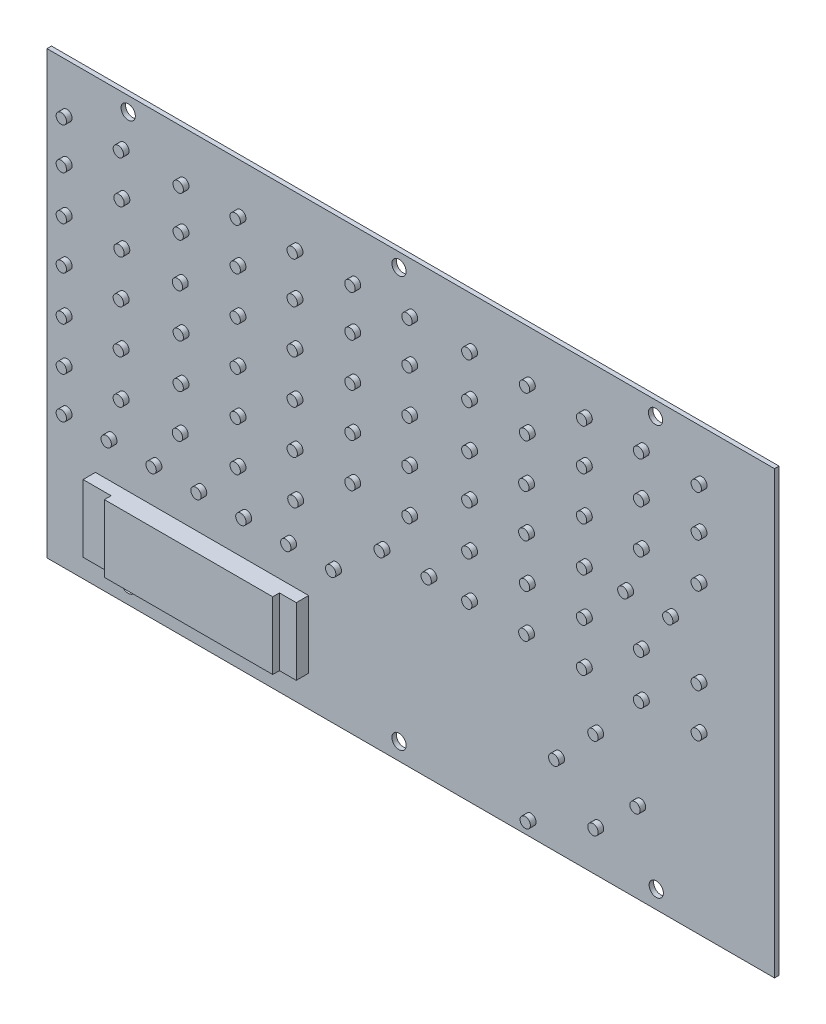
SolidWorks part; units mm, degrees
ref_plane "前视基准面" through (0, 0, 0) normal (0, 0, 1) x (1, 0, 0)
ref_plane "上视基准面" through (0, 0, 0) normal (0, 1, 0) x (1, 0, 0)
ref_plane "右视基准面" through (0, 0, 0) normal (1, 0, 0) x (0, 0, -1)
sketch "Model" plane through (0, 0, 0) normal (0, 0, 1) x (1, 0, 0)
  line L0 (148.209, 80.518) -> (148.1252, 80.518)
  line L1 (148.1252, 80.518) -> (134.874, 80.518)
  line L2 (134.874, 80.518) -> (18.542, 80.518)
  line L3 (101.092, 1.905) -> (18.542, 1.905)
  line L4 (18.542, 80.518) -> (18.542, 79.375)
  line L5 (18.542, 79.375) -> (18.542, 1.905)
  line L6 (18.542, 1.905) -> (18.763, 1.905)
  line L7 (148.209, 80.4342) -> (148.209, 80.518)
  line L8 (148.209, 80.518) -> (148.209, 1.905)
  line L9 (107.823, 1.905) -> (148.209, 1.905)
  line L10 (101.092, 1.905) -> (101.854, 1.905)
  line L11 (101.854, 1.905) -> (107.823, 1.905)
  line L12 (115.8771, 79.7949) -> (115.8771, 68.795)
  line L13 (121.1273, 79.7949) -> (115.8771, 79.7949)
  line L14 (121.1274, 68.7948) -> (115.8771, 68.7949)
  line L15 (121.1274, 68.7948) -> (121.427, 68.7948)
  line L16 (121.427, 68.7948) -> (121.427, 72.2638)
  line L17 (121.427, 76.326) -> (121.427, 79.805)
  line L18 (121.427, 79.805) -> (121.1273, 79.805)
  line L19 (140.208, 32.258) -> (142.7226, 32.258)
  line L20 (142.7226, 32.258) -> (142.7226, 27.178)
  line L21 (142.7226, 27.178) -> (140.208, 27.178)
  line L22 (140.208, 27.178) -> (140.208, 32.258)
  line L23 (143.891, 74.93) -> (143.891, 72.4154)
  line L24 (143.891, 72.4154) -> (138.811, 72.4154)
  line L25 (138.811, 72.4154) -> (138.811, 74.93)
  line L26 (138.811, 74.93) -> (143.891, 74.93)
  line L27 (130.2317, 51.816) -> (136.525, 45.5227)
  line L28 (136.525, 45.5227) -> (142.8183, 51.816)
  line L29 (142.8183, 51.816) -> (136.525, 58.1093)
  line L30 (136.525, 58.1093) -> (130.2317, 51.816)
  line L31 (144.146, 43.907) -> (144.146, 42.707)
  line L32 (146.196, 44.107) -> (147.196, 44.107)
  line L33 (146.196, 42.507) -> (147.196, 42.507)
  line L34 (145.3959, 44.107) -> (144.396, 44.107)
  line L35 (145.3959, 42.507) -> (144.396, 42.507)
  line L36 (147.446, 43.907) -> (147.446, 42.707)
  line L37 (147.246, 44.107) -> (147.196, 44.107)
  line L38 (147.246, 42.507) -> (147.196, 42.507)
  line L39 (144.346, 44.107) -> (144.396, 44.107)
  line L40 (144.346, 42.507) -> (144.396, 42.507)
  line L41 (144.146, 41.875) -> (144.146, 40.675)
  line L42 (146.196, 42.075) -> (147.196, 42.075)
  line L43 (146.196, 40.475) -> (147.196, 40.475)
  line L44 (145.3959, 42.075) -> (144.396, 42.075)
  line L45 (145.3959, 40.475) -> (144.396, 40.475)
  line L46 (147.446, 41.875) -> (147.446, 40.675)
  line L47 (147.246, 42.075) -> (147.196, 42.075)
  line L48 (147.246, 40.475) -> (147.196, 40.475)
  line L49 (144.346, 42.075) -> (144.396, 42.075)
  line L50 (144.346, 40.475) -> (144.396, 40.475)
  line L51 (144.146, 47.844) -> (144.146, 46.644)
  line L52 (146.196, 48.044) -> (147.196, 48.044)
  line L53 (146.196, 46.444) -> (147.196, 46.444)
  line L54 (145.3959, 48.044) -> (144.396, 48.044)
  line L55 (145.3959, 46.444) -> (144.396, 46.444)
  line L56 (147.446, 47.844) -> (147.446, 46.644)
  line L57 (147.246, 48.044) -> (147.196, 48.044)
  line L58 (147.246, 46.444) -> (147.196, 46.444)
  line L59 (144.346, 48.044) -> (144.396, 48.044)
  line L60 (144.346, 46.444) -> (144.396, 46.444)
  line L61 (144.146, 45.812) -> (144.146, 44.612)
  line L62 (146.196, 46.012) -> (147.196, 46.012)
  line L63 (146.196, 44.412) -> (147.196, 44.412)
  line L64 (145.3959, 46.012) -> (144.396, 46.012)
  line L65 (145.3959, 44.412) -> (144.396, 44.412)
  line L66 (147.446, 45.812) -> (147.446, 44.612)
  line L67 (147.246, 46.012) -> (147.196, 46.012)
  line L68 (147.246, 44.412) -> (147.196, 44.412)
  line L69 (144.346, 46.012) -> (144.396, 46.012)
  line L70 (144.346, 44.412) -> (144.396, 44.412)
  line L71 (139.061, 65.905) -> (139.061, 67.155)
  line L72 (141.101, 65.905) -> (141.101, 67.155)
  line L73 (139.061, 64.905) -> (139.061, 63.655)
  line L74 (141.101, 64.905) -> (141.101, 63.655)
  line L75 (139.061, 67.155) -> (141.101, 67.155)
  line L76 (139.061, 63.655) -> (141.101, 63.655)
  line L77 (141.347, 65.905) -> (141.347, 67.155)
  line L78 (143.387, 65.905) -> (143.387, 67.155)
  line L79 (141.347, 64.905) -> (141.347, 63.655)
  line L80 (143.387, 64.905) -> (143.387, 63.655)
  line L81 (141.347, 67.155) -> (143.387, 67.155)
  line L82 (141.347, 63.655) -> (143.387, 63.655)
  line L83 (132.426, 64.261) -> (131.226, 64.261)
  line L84 (132.626, 62.211) -> (132.626, 61.211)
  line L85 (131.026, 62.211) -> (131.026, 61.211)
  line L86 (132.626, 63.0111) -> (132.626, 64.011)
  line L87 (131.026, 63.0111) -> (131.026, 64.011)
  line L88 (132.426, 60.961) -> (131.226, 60.961)
  line L89 (132.626, 61.161) -> (132.626, 61.211)
  line L90 (131.026, 61.161) -> (131.026, 61.211)
  line L91 (132.626, 64.061) -> (132.626, 64.011)
  line L92 (131.026, 64.061) -> (131.026, 64.011)
  line L93 (143.983, 60.451) -> (142.783, 60.451)
  line L94 (144.183, 58.401) -> (144.183, 57.401)
  line L95 (142.583, 58.401) -> (142.583, 57.401)
  line L96 (144.183, 59.2011) -> (144.183, 60.201)
  line L97 (142.583, 59.2011) -> (142.583, 60.201)
  line L98 (143.983, 57.151) -> (142.783, 57.151)
  line L99 (144.183, 57.351) -> (144.183, 57.401)
  line L100 (142.583, 57.351) -> (142.583, 57.401)
  line L101 (144.183, 60.251) -> (144.183, 60.201)
  line L102 (142.583, 60.251) -> (142.583, 60.201)
  line L103 (139.354, 34.164) -> (140.554, 34.164)
  line L104 (139.154, 36.214) -> (139.154, 37.214)
  line L105 (140.754, 36.214) -> (140.754, 37.214)
  line L106 (139.154, 35.4139) -> (139.154, 34.414)
  line L107 (140.754, 35.4139) -> (140.754, 34.414)
  line L108 (139.354, 37.464) -> (140.554, 37.464)
  line L109 (139.154, 37.264) -> (139.154, 37.214)
  line L110 (140.754, 37.264) -> (140.754, 37.214)
  line L111 (139.154, 34.364) -> (139.154, 34.414)
  line L112 (140.754, 34.364) -> (140.754, 34.414)
  line L113 (141.513, 34.164) -> (142.713, 34.164)
  line L114 (141.313, 36.214) -> (141.313, 37.214)
  line L115 (142.913, 36.214) -> (142.913, 37.214)
  line L116 (141.313, 35.4139) -> (141.313, 34.414)
  line L117 (142.913, 35.4139) -> (142.913, 34.414)
  line L118 (141.513, 37.464) -> (142.713, 37.464)
  line L119 (141.313, 37.264) -> (141.313, 37.214)
  line L120 (142.913, 37.264) -> (142.913, 37.214)
  line L121 (141.313, 34.364) -> (141.313, 34.414)
  line L122 (142.913, 34.364) -> (142.913, 34.414)
  line L123 (145.5953, 81.4659) -> (145.9814, 81.885)
  line L124 (145.9814, 81.885) -> (145.6893, 81.885)
  line L125 (145.6893, 81.885) -> (145.0797, 81.2246)
  line L126 (145.0797, 81.2246) -> (138.065, 81.2246)
  line L127 (138.065, 81.2246) -> (137.4013, 81.9358)
  line L128 (137.4013, 81.9358) -> (137.2362, 81.9358)
  line L129 (137.2362, 81.9358) -> (137.2362, 81.885)
  line L130 (137.2362, 81.885) -> (137.5943, 81.4659)
  line L131 (137.6045, 75.9643) -> (139.8473, 75.9643)
  line L132 (143.3627, 75.9643) -> (145.6055, 75.9643)
  line L133 (145.6055, 79.9953) -> (145.6055, 81.5879)
  line L134 (137.6045, 79.9953) -> (137.6045, 81.4659)
  line L135 (137.6045, 79.9953) -> (137.6045, 79.9305)
  line L136 (137.6045, 78.1682) -> (137.6045, 77.3765)
  line L137 (137.6045, 76.0142) -> (137.6045, 75.9643)
  line L138 (145.6055, 79.9953) -> (145.6055, 79.9305)
  line L139 (145.6055, 78.1682) -> (145.6055, 77.3765)
  line L140 (145.6055, 76.0142) -> (145.6055, 75.9643)
  line L141 (138.9969, 41.8319) -> (143.1969, 41.8319)
  line L142 (143.1969, 41.8319) -> (143.1969, 38.4319)
  line L143 (143.1969, 38.4319) -> (138.9969, 38.4319)
  line L144 (138.9969, 38.4319) -> (138.9969, 41.8319)
  line L145 (20.823, 74.2591) -> (23.373, 74.2591)
  line L146 (24.348, 73.1779) -> (24.348, 70.8401)
  line L147 (23.3728, 69.7591) -> (20.8232, 69.7591)
  line L148 (19.848, 70.8401) -> (19.848, 73.1779)
  line L149 (20.823, 66.8931) -> (23.373, 66.8931)
  line L150 (24.348, 65.8119) -> (24.348, 63.4741)
  line L151 (23.3728, 62.3931) -> (20.8232, 62.3931)
  line L152 (19.848, 63.4741) -> (19.848, 65.8119)
  line L153 (20.823, 59.0191) -> (23.373, 59.0191)
  line L154 (24.348, 57.9379) -> (24.348, 55.6001)
  line L155 (23.3728, 54.5191) -> (20.8232, 54.5191)
  line L156 (19.848, 55.6001) -> (19.848, 57.9379)
  line L157 (20.823, 51.3991) -> (23.373, 51.3991)
  line L158 (24.348, 50.3179) -> (24.348, 47.9801)
  line L159 (23.3728, 46.8991) -> (20.8232, 46.8991)
  line L160 (19.848, 47.9801) -> (19.848, 50.3179)
  line L161 (20.823, 43.5251) -> (23.373, 43.5251)
  line L162 (24.348, 42.4439) -> (24.348, 40.1061)
  line L163 (23.3728, 39.0251) -> (20.8232, 39.0251)
  line L164 (19.848, 40.1061) -> (19.848, 42.4439)
  line L165 (20.823, 35.7781) -> (23.373, 35.7781)
  line L166 (24.348, 34.6969) -> (24.348, 32.3591)
  line L167 (23.3728, 31.2781) -> (20.8232, 31.2781)
  line L168 (19.848, 32.3591) -> (19.848, 34.6969)
  line L169 (20.823, 28.4121) -> (23.373, 28.4121)
  line L170 (24.348, 27.3309) -> (24.348, 24.9931)
  line L171 (23.3728, 23.9121) -> (20.8232, 23.9121)
  line L172 (19.848, 24.9931) -> (19.848, 27.3309)
  line L173 (28.824, 28.4121) -> (31.374, 28.4121)
  line L174 (32.349, 27.3309) -> (32.349, 24.9931)
  line L175 (31.3738, 23.9121) -> (28.8242, 23.9121)
  line L176 (27.849, 24.9931) -> (27.849, 27.3309)
  line L177 (30.983, 35.7781) -> (33.533, 35.7781)
  line L178 (34.508, 34.6969) -> (34.508, 32.3591)
  line L179 (33.5328, 31.2781) -> (30.9832, 31.2781)
  line L180 (30.008, 32.3591) -> (30.008, 34.6969)
  line L181 (30.983, 43.5251) -> (33.533, 43.5251)
  line L182 (34.508, 42.4439) -> (34.508, 40.1061)
  line L183 (33.5328, 39.0251) -> (30.9832, 39.0251)
  line L184 (30.008, 40.1061) -> (30.008, 42.4439)
  line L185 (30.983, 51.2721) -> (33.533, 51.2721)
  line L186 (34.508, 50.1909) -> (34.508, 47.8531)
  line L187 (33.5328, 46.7721) -> (30.9832, 46.7721)
  line L188 (30.008, 47.8531) -> (30.008, 50.1909)
  line L189 (31.11, 59.0191) -> (33.66, 59.0191)
  line L190 (34.635, 57.9379) -> (34.635, 55.6001)
  line L191 (33.6598, 54.5191) -> (31.1102, 54.5191)
  line L192 (30.135, 55.6001) -> (30.135, 57.9379)
  line L193 (31.11, 66.7661) -> (33.66, 66.7661)
  line L194 (34.635, 65.6849) -> (34.635, 63.3471)
  line L195 (33.6598, 62.2661) -> (31.1102, 62.2661)
  line L196 (30.135, 63.3471) -> (30.135, 65.6849)
  line L197 (30.983, 74.2591) -> (33.533, 74.2591)
  line L198 (34.508, 73.1779) -> (34.508, 70.8401)
  line L199 (33.5328, 69.7591) -> (30.9832, 69.7591)
  line L200 (30.008, 70.8401) -> (30.008, 73.1779)
  line L201 (36.825, 28.4121) -> (39.375, 28.4121)
  line L202 (40.35, 27.3309) -> (40.35, 24.9931)
  line L203 (39.3748, 23.9121) -> (36.8252, 23.9121)
  line L204 (35.85, 24.9931) -> (35.85, 27.3309)
  line L205 (41.524, 35.7781) -> (44.074, 35.7781)
  line L206 (45.049, 34.6969) -> (45.049, 32.3591)
  line L207 (44.0738, 31.2781) -> (41.5242, 31.2781)
  line L208 (40.549, 32.3591) -> (40.549, 34.6969)
  line L209 (41.651, 43.5251) -> (44.201, 43.5251)
  line L210 (45.176, 42.4439) -> (45.176, 40.1061)
  line L211 (44.2008, 39.0251) -> (41.6512, 39.0251)
  line L212 (40.676, 40.1061) -> (40.676, 42.4439)
  line L213 (41.651, 51.2721) -> (44.201, 51.2721)
  line L214 (45.176, 50.1909) -> (45.176, 47.8531)
  line L215 (44.2008, 46.7721) -> (41.6512, 46.7721)
  line L216 (40.676, 47.8531) -> (40.676, 50.1909)
  line L217 (41.524, 59.0191) -> (44.074, 59.0191)
  line L218 (45.049, 57.9379) -> (45.049, 55.6001)
  line L219 (44.0738, 54.5191) -> (41.5242, 54.5191)
  line L220 (40.549, 55.6001) -> (40.549, 57.9379)
  line L221 (41.651, 66.8931) -> (44.201, 66.8931)
  line L222 (45.176, 65.8119) -> (45.176, 63.4741)
  line L223 (44.2008, 62.3931) -> (41.6512, 62.3931)
  line L224 (40.676, 63.4741) -> (40.676, 65.8119)
  line L225 (41.651, 74.1321) -> (44.201, 74.1321)
  line L226 (45.176, 73.0509) -> (45.176, 70.7131)
  line L227 (44.2008, 69.6321) -> (41.6512, 69.6321)
  line L228 (40.676, 70.7131) -> (40.676, 73.0509)
  line L229 (44.826, 28.4121) -> (47.376, 28.4121)
  line L230 (48.351, 27.3309) -> (48.351, 24.9931)
  line L231 (47.3758, 23.9121) -> (44.8262, 23.9121)
  line L232 (43.851, 24.9931) -> (43.851, 27.3309)
  line L233 (51.811, 35.7781) -> (54.361, 35.7781)
  line L234 (55.336, 34.6969) -> (55.336, 32.3591)
  line L235 (54.3608, 31.2781) -> (51.8112, 31.2781)
  line L236 (50.836, 32.3591) -> (50.836, 34.6969)
  line L237 (51.811, 43.5251) -> (54.361, 43.5251)
  line L238 (55.336, 42.4439) -> (55.336, 40.1061)
  line L239 (54.3608, 39.0251) -> (51.8112, 39.0251)
  line L240 (50.836, 40.1061) -> (50.836, 42.4439)
  line L241 (51.811, 51.2721) -> (54.361, 51.2721)
  line L242 (55.336, 50.1909) -> (55.336, 47.8531)
  line L243 (54.3608, 46.7721) -> (51.8112, 46.7721)
  line L244 (50.836, 47.8531) -> (50.836, 50.1909)
  line L245 (51.811, 59.0191) -> (54.361, 59.0191)
  line L246 (55.336, 57.9379) -> (55.336, 55.6001)
  line L247 (54.3608, 54.5191) -> (51.8112, 54.5191)
  line L248 (50.836, 55.6001) -> (50.836, 57.9379)
  line L249 (51.811, 66.7661) -> (54.361, 66.7661)
  line L250 (55.336, 65.6849) -> (55.336, 63.3471)
  line L251 (54.3608, 62.2661) -> (51.8112, 62.2661)
  line L252 (50.836, 63.3471) -> (50.836, 65.6849)
  line L253 (51.811, 74.2591) -> (54.361, 74.2591)
  line L254 (55.336, 73.1779) -> (55.336, 70.8401)
  line L255 (54.3608, 69.7591) -> (51.8112, 69.7591)
  line L256 (50.836, 70.8401) -> (50.836, 73.1779)
  line L257 (52.827, 28.4121) -> (55.377, 28.4121)
  line L258 (56.352, 27.3309) -> (56.352, 24.9931)
  line L259 (55.3768, 23.9121) -> (52.8272, 23.9121)
  line L260 (51.852, 24.9931) -> (51.852, 27.3309)
  line L261 (62.098, 35.7781) -> (64.648, 35.7781)
  line L262 (65.623, 34.6969) -> (65.623, 32.3591)
  line L263 (64.6478, 31.2781) -> (62.0982, 31.2781)
  line L264 (61.123, 32.3591) -> (61.123, 34.6969)
  line L265 (61.971, 43.5251) -> (64.521, 43.5251)
  line L266 (65.496, 42.4439) -> (65.496, 40.1061)
  line L267 (64.5208, 39.0251) -> (61.9712, 39.0251)
  line L268 (60.996, 40.1061) -> (60.996, 42.4439)
  line L269 (61.971, 51.2721) -> (64.521, 51.2721)
  line L270 (65.496, 50.1909) -> (65.496, 47.8531)
  line L271 (64.5208, 46.7721) -> (61.9712, 46.7721)
  line L272 (60.996, 47.8531) -> (60.996, 50.1909)
  line L273 (61.971, 59.0191) -> (64.521, 59.0191)
  line L274 (65.496, 57.9379) -> (65.496, 55.6001)
  line L275 (64.5208, 54.5191) -> (61.9712, 54.5191)
  line L276 (60.996, 55.6001) -> (60.996, 57.9379)
  line L277 (61.971, 66.7661) -> (64.521, 66.7661)
  line L278 (65.496, 65.6849) -> (65.496, 63.3471)
  line L279 (64.5208, 62.2661) -> (61.9712, 62.2661)
  line L280 (60.996, 63.3471) -> (60.996, 65.6849)
  line L281 (61.971, 74.1321) -> (64.521, 74.1321)
  line L282 (65.496, 73.0509) -> (65.496, 70.7131)
  line L283 (64.5208, 69.6321) -> (61.9712, 69.6321)
  line L284 (60.996, 70.7131) -> (60.996, 73.0509)
  line L285 (60.828, 28.4121) -> (63.378, 28.4121)
  line L286 (64.353, 27.3309) -> (64.353, 24.9931)
  line L287 (63.3778, 23.9121) -> (60.8282, 23.9121)
  line L288 (59.853, 24.9931) -> (59.853, 27.3309)
  line L289 (77.465, 35.7781) -> (80.015, 35.7781)
  line L290 (80.99, 34.6969) -> (80.99, 32.3591)
  line L291 (80.0148, 31.2781) -> (77.4652, 31.2781)
  line L292 (76.49, 32.3591) -> (76.49, 34.6969)
  line L293 (72.258, 43.5251) -> (74.808, 43.5251)
  line L294 (75.783, 42.4439) -> (75.783, 40.1061)
  line L295 (74.8078, 39.0251) -> (72.2582, 39.0251)
  line L296 (71.283, 40.1061) -> (71.283, 42.4439)
  line L297 (72.258, 51.2721) -> (74.808, 51.2721)
  line L298 (75.783, 50.1909) -> (75.783, 47.8531)
  line L299 (74.8078, 46.7721) -> (72.2582, 46.7721)
  line L300 (71.283, 47.8531) -> (71.283, 50.1909)
  line L301 (72.258, 59.0191) -> (74.808, 59.0191)
  line L302 (75.783, 57.9379) -> (75.783, 55.6001)
  line L303 (74.8078, 54.5191) -> (72.2582, 54.5191)
  line L304 (71.283, 55.6001) -> (71.283, 57.9379)
  line L305 (72.258, 66.7661) -> (74.808, 66.7661)
  line L306 (75.783, 65.6849) -> (75.783, 63.3471)
  line L307 (74.8078, 62.2661) -> (72.2582, 62.2661)
  line L308 (71.283, 63.3471) -> (71.283, 65.6849)
  line L309 (72.258, 74.1321) -> (74.808, 74.1321)
  line L310 (75.783, 73.0509) -> (75.783, 70.7131)
  line L311 (74.8078, 69.6321) -> (72.2582, 69.6321)
  line L312 (71.283, 70.7131) -> (71.283, 73.0509)
  line L313 (68.829, 28.4121) -> (71.379, 28.4121)
  line L314 (72.354, 27.3309) -> (72.354, 24.9931)
  line L315 (71.3788, 23.9121) -> (68.8292, 23.9121)
  line L316 (67.854, 24.9931) -> (67.854, 27.3309)
  line L317 (85.847, 35.7781) -> (88.397, 35.7781)
  line L318 (89.372, 34.6969) -> (89.372, 32.3591)
  line L319 (88.3968, 31.2781) -> (85.8472, 31.2781)
  line L320 (84.872, 32.3591) -> (84.872, 34.6969)
  line L321 (82.418, 43.5251) -> (84.968, 43.5251)
  line L322 (85.943, 42.4439) -> (85.943, 40.1061)
  line L323 (84.9678, 39.0251) -> (82.4182, 39.0251)
  line L324 (81.443, 40.1061) -> (81.443, 42.4439)
  line L325 (82.418, 51.2721) -> (84.968, 51.2721)
  line L326 (85.943, 50.1909) -> (85.943, 47.8531)
  line L327 (84.9678, 46.7721) -> (82.4182, 46.7721)
  line L328 (81.443, 47.8531) -> (81.443, 50.1909)
  line L329 (82.418, 59.0191) -> (84.968, 59.0191)
  line L330 (85.943, 57.9379) -> (85.943, 55.6001)
  line L331 (84.9678, 54.5191) -> (82.4182, 54.5191)
  line L332 (81.443, 55.6001) -> (81.443, 57.9379)
  line L333 (82.418, 66.7661) -> (84.968, 66.7661)
  line L334 (85.943, 65.6849) -> (85.943, 63.3471)
  line L335 (84.9678, 62.2661) -> (82.4182, 62.2661)
  line L336 (81.443, 63.3471) -> (81.443, 65.6849)
  line L337 (82.418, 74.1321) -> (84.968, 74.1321)
  line L338 (85.943, 73.0509) -> (85.943, 70.7131)
  line L339 (84.9678, 69.6321) -> (82.4182, 69.6321)
  line L340 (81.443, 70.7131) -> (81.443, 73.0509)
  line L341 (103.5, 6.9491) -> (106.05, 6.9491)
  line L342 (107.025, 5.8679) -> (107.025, 3.5301)
  line L343 (106.0498, 2.4491) -> (103.5002, 2.4491)
  line L344 (102.525, 3.5301) -> (102.525, 5.8679)
  line L345 (93.086, 35.6511) -> (95.636, 35.6511)
  line L346 (96.611, 34.5699) -> (96.611, 32.2321)
  line L347 (95.6358, 31.1511) -> (93.0862, 31.1511)
  line L348 (92.111, 32.2321) -> (92.111, 34.5699)
  line L349 (93.086, 43.3981) -> (95.636, 43.3981)
  line L350 (96.611, 42.3169) -> (96.611, 39.9791)
  line L351 (95.6358, 38.8981) -> (93.0862, 38.8981)
  line L352 (92.111, 39.9791) -> (92.111, 42.3169)
  line L353 (93.086, 51.2721) -> (95.636, 51.2721)
  line L354 (96.611, 50.1909) -> (96.611, 47.8531)
  line L355 (95.6358, 46.7721) -> (93.0862, 46.7721)
  line L356 (92.111, 47.8531) -> (92.111, 50.1909)
  line L357 (93.086, 58.8921) -> (95.636, 58.8921)
  line L358 (96.611, 57.8109) -> (96.611, 55.4731)
  line L359 (95.6358, 54.3921) -> (93.0862, 54.3921)
  line L360 (92.111, 55.4731) -> (92.111, 57.8109)
  line L361 (93.086, 66.7661) -> (95.636, 66.7661)
  line L362 (96.611, 65.6849) -> (96.611, 63.3471)
  line L363 (95.6358, 62.2661) -> (93.0862, 62.2661)
  line L364 (92.111, 63.3471) -> (92.111, 65.6849)
  line L365 (93.086, 74.1321) -> (95.636, 74.1321)
  line L366 (96.611, 73.0509) -> (96.611, 70.7131)
  line L367 (95.6358, 69.6321) -> (93.0862, 69.6321)
  line L368 (92.111, 70.7131) -> (92.111, 73.0509)
  line L369 (108.58, 19.1411) -> (111.13, 19.1411)
  line L370 (112.105, 18.0599) -> (112.105, 15.7221)
  line L371 (111.1298, 14.6411) -> (108.5802, 14.6411)
  line L372 (107.605, 15.7221) -> (107.605, 18.0599)
  line L373 (103.246, 35.7781) -> (105.796, 35.7781)
  line L374 (106.771, 34.6969) -> (106.771, 32.3591)
  line L375 (105.7958, 31.2781) -> (103.2462, 31.2781)
  line L376 (102.271, 32.3591) -> (102.271, 34.6969)
  line L377 (103.373, 43.5251) -> (105.923, 43.5251)
  line L378 (106.898, 42.4439) -> (106.898, 40.1061)
  line L379 (105.9228, 39.0251) -> (103.3732, 39.0251)
  line L380 (102.398, 40.1061) -> (102.398, 42.4439)
  line L381 (103.246, 51.2721) -> (105.796, 51.2721)
  line L382 (106.771, 50.1909) -> (106.771, 47.8531)
  line L383 (105.7958, 46.7721) -> (103.2462, 46.7721)
  line L384 (102.271, 47.8531) -> (102.271, 50.1909)
  line L385 (103.246, 58.8921) -> (105.796, 58.8921)
  line L386 (106.771, 57.8109) -> (106.771, 55.4731)
  line L387 (105.7958, 54.3921) -> (103.2462, 54.3921)
  line L388 (102.271, 55.4731) -> (102.271, 57.8109)
  line L389 (103.373, 66.7661) -> (105.923, 66.7661)
  line L390 (106.898, 65.6849) -> (106.898, 63.3471)
  line L391 (105.9228, 62.2661) -> (103.3732, 62.2661)
  line L392 (102.398, 63.3471) -> (102.398, 65.6849)
  line L393 (103.373, 74.1321) -> (105.923, 74.1321)
  line L394 (106.898, 73.0509) -> (106.898, 70.7131)
  line L395 (105.9228, 69.6321) -> (103.3732, 69.6321)
  line L396 (102.398, 70.7131) -> (102.398, 73.0509)
  line L397 (115.565, 26.5071) -> (118.115, 26.5071)
  line L398 (119.09, 25.4259) -> (119.09, 23.0881)
  line L399 (118.1148, 22.0071) -> (115.5652, 22.0071)
  line L400 (114.59, 23.0881) -> (114.59, 25.4259)
  line L401 (113.533, 35.6511) -> (116.083, 35.6511)
  line L402 (117.058, 34.5699) -> (117.058, 32.2321)
  line L403 (116.0828, 31.1511) -> (113.5332, 31.1511)
  line L404 (112.558, 32.2321) -> (112.558, 34.5699)
  line L405 (113.533, 43.3981) -> (116.083, 43.3981)
  line L406 (117.058, 42.3169) -> (117.058, 39.9791)
  line L407 (116.0828, 38.8981) -> (113.5332, 38.8981)
  line L408 (112.558, 39.9791) -> (112.558, 42.3169)
  line L409 (113.533, 51.1451) -> (116.083, 51.1451)
  line L410 (117.058, 50.0639) -> (117.058, 47.7261)
  line L411 (116.0828, 46.6451) -> (113.5332, 46.6451)
  line L412 (112.558, 47.7261) -> (112.558, 50.0639)
  line L413 (113.533, 59.0191) -> (116.083, 59.0191)
  line L414 (117.058, 57.9379) -> (117.058, 55.6001)
  line L415 (116.0828, 54.5191) -> (113.5332, 54.5191)
  line L416 (112.558, 55.6001) -> (112.558, 57.9379)
  line L417 (113.533, 66.7661) -> (116.083, 66.7661)
  line L418 (117.058, 65.6849) -> (117.058, 63.3471)
  line L419 (116.0828, 62.2661) -> (113.5332, 62.2661)
  line L420 (112.558, 63.3471) -> (112.558, 65.6849)
  line L421 (113.533, 74.1321) -> (116.083, 74.1321)
  line L422 (117.058, 73.0509) -> (117.058, 70.7131)
  line L423 (116.0828, 69.6321) -> (113.5332, 69.6321)
  line L424 (112.558, 70.7131) -> (112.558, 73.0509)
  line L425 (123.058, 19.0141) -> (125.608, 19.0141)
  line L426 (126.583, 17.9329) -> (126.583, 15.5951)
  line L427 (125.6078, 14.5141) -> (123.0582, 14.5141)
  line L428 (122.083, 15.5951) -> (122.083, 17.9329)
  line L429 (123.693, 35.6511) -> (126.243, 35.6511)
  line L430 (127.218, 34.5699) -> (127.218, 32.2321)
  line L431 (126.2428, 31.1511) -> (123.6932, 31.1511)
  line L432 (122.718, 32.2321) -> (122.718, 34.5699)
  line L433 (123.693, 43.5251) -> (126.243, 43.5251)
  line L434 (127.218, 42.4439) -> (127.218, 40.1061)
  line L435 (126.2428, 39.0251) -> (123.6932, 39.0251)
  line L436 (122.718, 40.1061) -> (122.718, 42.4439)
  line L437 (120.899, 51.1451) -> (123.449, 51.1451)
  line L438 (124.424, 50.0639) -> (124.424, 47.7261)
  line L439 (123.4488, 46.6451) -> (120.8992, 46.6451)
  line L440 (119.924, 47.7261) -> (119.924, 50.0639)
  line L441 (123.693, 59.0191) -> (126.243, 59.0191)
  line L442 (127.218, 57.9379) -> (127.218, 55.6001)
  line L443 (126.2428, 54.5191) -> (123.6932, 54.5191)
  line L444 (122.718, 55.6001) -> (122.718, 57.9379)
  line L445 (123.693, 66.7661) -> (126.243, 66.7661)
  line L446 (127.218, 65.6849) -> (127.218, 63.3471)
  line L447 (126.2428, 62.2661) -> (123.6932, 62.2661)
  line L448 (122.718, 63.3471) -> (122.718, 65.6849)
  line L449 (123.693, 74.1321) -> (126.243, 74.1321)
  line L450 (127.218, 73.0509) -> (127.218, 70.7131)
  line L451 (126.2428, 69.6321) -> (123.6932, 69.6321)
  line L452 (122.718, 70.7131) -> (122.718, 73.0509)
  line L453 (115.565, 11.9021) -> (118.115, 11.9021)
  line L454 (119.09, 10.8209) -> (119.09, 8.4831)
  line L455 (118.1148, 7.4021) -> (115.5652, 7.4021)
  line L456 (114.59, 8.4831) -> (114.59, 10.8209)
  line L457 (133.98, 35.7781) -> (136.53, 35.7781)
  line L458 (137.505, 34.6969) -> (137.505, 32.3591)
  line L459 (136.5298, 31.2781) -> (133.9802, 31.2781)
  line L460 (133.005, 32.3591) -> (133.005, 34.6969)
  line L461 (133.98, 43.5251) -> (136.53, 43.5251)
  line L462 (137.505, 42.4439) -> (137.505, 40.1061)
  line L463 (136.5298, 39.0251) -> (133.9802, 39.0251)
  line L464 (133.005, 40.1061) -> (133.005, 42.4439)
  line L465 (128.9, 51.1451) -> (131.45, 51.1451)
  line L466 (132.425, 50.0639) -> (132.425, 47.7261)
  line L467 (131.4498, 46.6451) -> (128.9002, 46.6451)
  line L468 (127.925, 47.7261) -> (127.925, 50.0639)
  line L469 (133.98, 58.8921) -> (136.53, 58.8921)
  line L470 (137.505, 57.8109) -> (137.505, 55.4731)
  line L471 (136.5298, 54.3921) -> (133.9802, 54.3921)
  line L472 (133.005, 55.4731) -> (133.005, 57.8109)
  line L473 (133.98, 66.7661) -> (136.53, 66.7661)
  line L474 (137.505, 65.6849) -> (137.505, 63.3471)
  line L475 (136.5298, 62.2661) -> (133.9802, 62.2661)
  line L476 (133.005, 63.3471) -> (133.005, 65.6849)
  line L477 (133.98, 74.1321) -> (136.53, 74.1321)
  line L478 (137.505, 73.0509) -> (137.505, 70.7131)
  line L479 (136.5298, 69.6321) -> (133.9802, 69.6321)
  line L480 (133.005, 70.7131) -> (133.005, 73.0509)
  line L481 (28.575, 19.05) -> (28.575, 7.62)
  line L482 (28.575, 7.62) -> (47.625, 7.62)
  line L483 (47.625, 7.62) -> (66.675, 7.62)
  line L484 (66.675, 7.62) -> (66.7748, 19.5199)
  line L485 (66.7748, 19.5199) -> (28.575, 19.5199)
  line L486 (28.575, 19.5199) -> (28.575, 19.05)
  line L487 (131.191, 71.12) -> (128.6764, 71.12)
  line L488 (128.6764, 71.12) -> (128.6764, 66.04)
  line L489 (128.6764, 66.04) -> (131.191, 66.04)
  line L490 (131.191, 66.04) -> (131.191, 71.12)
  line L491 (120.6769, 75.4949) -> (120.6769, 76.0949)
  line L492 (120.6769, 76.0949) -> (122.8769, 76.0949)
  line L493 (122.8769, 76.0949) -> (122.8769, 75.4949)
  line L494 (122.8769, 75.4949) -> (120.6769, 75.4949)
  line L495 (120.6769, 74.4949) -> (120.6769, 75.0949)
  line L496 (120.6769, 75.0949) -> (122.8769, 75.0949)
  line L497 (122.8769, 75.0949) -> (122.8769, 74.4949)
  line L498 (122.8769, 74.4949) -> (120.6769, 74.4949)
  line L499 (120.6769, 73.4949) -> (120.6769, 74.0949)
  line L500 (120.6769, 74.0949) -> (122.8769, 74.0949)
  line L501 (122.8769, 74.0949) -> (122.8769, 73.4949)
  line L502 (122.8769, 73.4949) -> (120.6769, 73.4949)
  line L503 (120.6769, 72.4949) -> (120.6769, 73.0949)
  line L504 (120.6769, 73.0949) -> (122.8769, 73.0949)
  line L505 (122.8769, 73.0949) -> (122.8769, 72.4949)
  line L506 (122.8769, 72.4949) -> (120.6769, 72.4949)
  line L507 (121.0769, 69.1949) -> (121.0769, 71.7949)
  line L508 (121.0769, 71.7949) -> (118.477, 71.7949)
  line L509 (118.477, 71.7949) -> (118.477, 69.1949)
  line L510 (118.477, 69.1949) -> (121.0769, 69.1949)
  line L511 (121.0769, 76.7949) -> (121.0769, 79.3949)
  line L512 (121.0769, 79.3949) -> (118.477, 79.3949)
  line L513 (118.477, 79.3949) -> (118.477, 76.7949)
  line L514 (118.477, 76.7949) -> (121.0769, 76.7949)
  line L515 (140.6906, 29.2354) -> (142.2654, 29.2354)
  line L516 (142.2654, 29.2354) -> (142.2654, 27.6606)
  line L517 (142.2654, 27.6606) -> (140.6906, 27.6606)
  line L518 (140.6906, 27.6606) -> (140.6906, 29.2354)
  line L519 (140.8684, 74.4474) -> (140.8684, 72.8726)
  line L520 (140.8684, 72.8726) -> (139.2936, 72.8726)
  line L521 (139.2936, 72.8726) -> (139.2936, 74.4474)
  line L522 (139.2936, 74.4474) -> (140.8684, 74.4474)
  line L523 (137.1259, 58.3707) -> (137.9603, 59.2051)
  line L524 (137.9603, 59.2051) -> (137.1259, 58.3707)
  line L525 (137.4229, 58.0738) -> (138.2573, 58.9082)
  line L526 (138.2573, 58.9082) -> (137.4229, 58.0738)
  line L527 (137.6918, 57.8051) -> (138.5262, 58.6395)
  line L528 (138.5262, 58.6395) -> (137.6918, 57.8051)
  line L529 (137.9888, 57.5081) -> (138.8232, 58.3425)
  line L530 (138.8232, 58.3425) -> (137.9888, 57.5081)
  line L531 (138.2573, 57.2394) -> (139.0916, 58.0738)
  line L532 (139.0916, 58.0738) -> (138.2573, 57.2394)
  line L533 (138.5542, 56.9425) -> (139.3886, 57.7768)
  line L534 (139.3886, 57.7768) -> (138.5542, 56.9425)
  line L535 (138.8232, 56.6738) -> (139.6576, 57.5082)
  line L536 (139.6576, 57.5082) -> (138.8232, 56.6738)
  line L537 (139.1201, 56.3768) -> (139.9545, 57.2112)
  line L538 (139.9545, 57.2112) -> (139.1201, 56.3768)
  line L539 (139.3886, 56.1081) -> (140.223, 56.9425)
  line L540 (140.223, 56.9425) -> (139.3886, 56.1081)
  line L541 (139.6855, 55.8111) -> (140.5199, 56.6455)
  line L542 (140.5199, 56.6455) -> (139.6855, 55.8111)
  line L543 (139.9545, 55.5425) -> (140.7889, 56.3769)
  line L544 (140.7889, 56.3769) -> (139.9545, 55.5425)
  line L545 (140.2515, 55.2455) -> (141.0859, 56.0799)
  line L546 (141.0859, 56.0799) -> (140.2515, 55.2455)
  line L547 (140.5201, 54.9765) -> (141.3545, 55.8109)
  line L548 (141.3545, 55.8109) -> (140.5201, 54.9765)
  line L549 (140.8171, 54.6796) -> (141.6515, 55.514)
  line L550 (141.6515, 55.514) -> (140.8171, 54.6796)
  line L551 (141.0858, 54.4111) -> (141.9202, 55.2455)
  line L552 (141.9202, 55.2455) -> (141.0858, 54.4111)
  line L553 (141.3828, 54.1142) -> (142.2172, 54.9486)
  line L554 (142.2172, 54.9486) -> (141.3828, 54.1142)
  line L555 (141.6515, 53.8452) -> (142.4858, 54.6796)
  line L556 (142.4858, 54.6796) -> (141.6515, 53.8452)
  line L557 (141.9484, 53.5483) -> (142.7828, 54.3826)
  line L558 (142.7828, 54.3826) -> (141.9484, 53.5483)
  line L559 (142.2171, 53.2798) -> (143.0515, 54.1142)
  line L560 (143.0515, 54.1142) -> (142.2171, 53.2798)
  line L561 (142.5141, 52.9828) -> (143.3485, 53.8172)
  line L562 (143.3485, 53.8172) -> (142.5141, 52.9828)
  line L563 (142.7828, 52.7139) -> (143.6172, 53.5483)
  line L564 (143.6172, 53.5483) -> (142.7828, 52.7139)
  line L565 (143.0797, 52.4169) -> (143.9141, 53.2513)
  line L566 (143.9141, 53.2513) -> (143.0797, 52.4169)
  line L567 (143.6172, 50.0837) -> (142.7828, 50.9181)
  line L568 (142.7828, 50.9181) -> (143.6172, 50.0837)
  line L569 (143.9141, 50.3807) -> (143.0797, 51.2151)
  line L570 (143.0797, 51.2151) -> (143.9141, 50.3807)
  line L571 (143.0515, 49.5178) -> (142.2171, 50.3522)
  line L572 (142.2171, 50.3522) -> (143.0515, 49.5178)
  line L573 (143.3485, 49.8148) -> (142.5141, 50.6492)
  line L574 (142.5141, 50.6492) -> (143.3485, 49.8148)
  line L575 (142.4858, 48.9524) -> (141.6515, 49.7868)
  line L576 (141.6515, 49.7868) -> (142.4858, 48.9524)
  line L577 (142.7828, 49.2494) -> (141.9484, 50.0837)
  line L578 (141.9484, 50.0837) -> (142.7828, 49.2494)
  line L579 (141.9202, 48.3865) -> (141.0858, 49.2209)
  line L580 (141.0858, 49.2209) -> (141.9202, 48.3865)
  line L581 (142.2172, 48.6834) -> (141.3828, 49.5178)
  line L582 (141.3828, 49.5178) -> (142.2172, 48.6834)
  line L583 (141.3545, 47.8208) -> (140.5201, 48.6552)
  line L584 (140.5201, 48.6552) -> (141.3545, 47.8208)
  line L585 (141.6515, 48.1178) -> (140.8171, 48.9522)
  line L586 (140.8171, 48.9522) -> (141.6515, 48.1178)
  line L587 (140.7889, 47.2551) -> (139.9545, 48.0895)
  line L588 (139.9545, 48.0895) -> (140.7889, 47.2551)
  line L589 (141.0859, 47.5521) -> (140.2515, 48.3865)
  line L590 (140.2515, 48.3865) -> (141.0859, 47.5521)
  line L591 (140.223, 46.6895) -> (139.3886, 47.5239)
  line L592 (139.3886, 47.5239) -> (140.223, 46.6895)
  line L593 (140.5199, 46.9865) -> (139.6855, 47.8209)
  line L594 (139.6855, 47.8209) -> (140.5199, 46.9865)
  line L595 (139.6576, 46.1238) -> (138.8232, 46.9582)
  line L596 (138.8232, 46.9582) -> (139.6576, 46.1238)
  line L597 (139.9545, 46.4208) -> (139.1201, 47.2552)
  line L598 (139.1201, 47.2552) -> (139.9545, 46.4208)
  line L599 (139.0916, 45.5582) -> (138.2573, 46.3926)
  line L600 (138.2573, 46.3926) -> (139.0916, 45.5582)
  line L601 (139.3886, 45.8552) -> (138.5542, 46.6895)
  line L602 (138.5542, 46.6895) -> (139.3886, 45.8552)
  line L603 (138.5262, 44.9925) -> (137.6918, 45.8269)
  line L604 (137.6918, 45.8269) -> (138.5262, 44.9925)
  line L605 (138.8232, 45.2895) -> (137.9888, 46.1239)
  line L606 (137.9888, 46.1239) -> (138.8232, 45.2895)
  line L607 (137.9603, 44.4269) -> (137.1259, 45.2613)
  line L608 (137.1259, 45.2613) -> (137.9603, 44.4269)
  line L609 (138.2573, 44.7238) -> (137.4229, 45.5582)
  line L610 (137.4229, 45.5582) -> (138.2573, 44.7238)
  line L611 (134.7927, 44.7238) -> (135.6271, 45.5582)
  line L612 (135.6271, 45.5582) -> (134.7927, 44.7238)
  line L613 (135.0897, 44.4269) -> (135.9241, 45.2613)
  line L614 (135.9241, 45.2613) -> (135.0897, 44.4269)
  line L615 (134.2268, 45.2895) -> (135.0612, 46.1239)
  line L616 (135.0612, 46.1239) -> (134.2268, 45.2895)
  line L617 (134.5238, 44.9925) -> (135.3582, 45.8269)
  line L618 (135.3582, 45.8269) -> (134.5238, 44.9925)
  line L619 (133.6614, 45.8552) -> (134.4958, 46.6895)
  line L620 (134.4958, 46.6895) -> (133.6614, 45.8552)
  line L621 (133.9584, 45.5582) -> (134.7927, 46.3926)
  line L622 (134.7927, 46.3926) -> (133.9584, 45.5582)
  line L623 (133.0955, 46.4208) -> (133.9299, 47.2552)
  line L624 (133.9299, 47.2552) -> (133.0955, 46.4208)
  line L625 (133.3924, 46.1238) -> (134.2268, 46.9582)
  line L626 (134.2268, 46.9582) -> (133.3924, 46.1238)
  line L627 (132.5298, 46.9865) -> (133.3642, 47.8209)
  line L628 (133.3642, 47.8209) -> (132.5298, 46.9865)
  line L629 (132.8268, 46.6895) -> (133.6612, 47.5239)
  line L630 (133.6612, 47.5239) -> (132.8268, 46.6895)
  line L631 (131.9641, 47.5521) -> (132.7985, 48.3865)
  line L632 (132.7985, 48.3865) -> (131.9641, 47.5521)
  line L633 (132.2611, 47.2551) -> (133.0955, 48.0895)
  line L634 (133.0955, 48.0895) -> (132.2611, 47.2551)
  line L635 (131.3985, 48.1178) -> (132.2329, 48.9522)
  line L636 (132.2329, 48.9522) -> (131.3985, 48.1178)
  line L637 (131.6955, 47.8208) -> (132.5299, 48.6552)
  line L638 (132.5299, 48.6552) -> (131.6955, 47.8208)
  line L639 (130.8328, 48.6834) -> (131.6672, 49.5178)
  line L640 (131.6672, 49.5178) -> (130.8328, 48.6834)
  line L641 (131.1298, 48.3865) -> (131.9642, 49.2209)
  line L642 (131.9642, 49.2209) -> (131.1298, 48.3865)
  line L643 (130.2672, 49.2494) -> (131.1016, 50.0837)
  line L644 (131.1016, 50.0837) -> (130.2672, 49.2494)
  line L645 (130.5642, 48.9524) -> (131.3985, 49.7868)
  line L646 (131.3985, 49.7868) -> (130.5642, 48.9524)
  line L647 (129.7015, 49.8148) -> (130.5359, 50.6492)
  line L648 (130.5359, 50.6492) -> (129.7015, 49.8148)
  line L649 (129.9985, 49.5178) -> (130.8329, 50.3522)
  line L650 (130.8329, 50.3522) -> (129.9985, 49.5178)
  line L651 (129.1359, 50.3807) -> (129.9703, 51.2151)
  line L652 (129.9703, 51.2151) -> (129.1359, 50.3807)
  line L653 (129.4328, 50.0837) -> (130.2672, 50.9181)
  line L654 (130.2672, 50.9181) -> (129.4328, 50.0837)
  line L655 (129.9703, 52.4169) -> (129.1359, 53.2513)
  line L656 (129.1359, 53.2513) -> (129.9703, 52.4169)
  line L657 (130.2672, 52.7139) -> (129.4328, 53.5483)
  line L658 (129.4328, 53.5483) -> (130.2672, 52.7139)
  line L659 (130.5359, 52.9828) -> (129.7015, 53.8172)
  line L660 (129.7015, 53.8172) -> (130.5359, 52.9828)
  line L661 (130.8329, 53.2798) -> (129.9985, 54.1142)
  line L662 (129.9985, 54.1142) -> (130.8329, 53.2798)
  line L663 (131.1016, 53.5483) -> (130.2672, 54.3826)
  line L664 (130.2672, 54.3826) -> (131.1016, 53.5483)
  line L665 (131.3985, 53.8452) -> (130.5642, 54.6796)
  line L666 (130.5642, 54.6796) -> (131.3985, 53.8452)
  line L667 (131.6672, 54.1142) -> (130.8328, 54.9486)
  line L668 (130.8328, 54.9486) -> (131.6672, 54.1142)
  line L669 (131.9642, 54.4111) -> (131.1298, 55.2455)
  line L670 (131.1298, 55.2455) -> (131.9642, 54.4111)
  line L671 (132.2329, 54.6796) -> (131.3985, 55.514)
  line L672 (131.3985, 55.514) -> (132.2329, 54.6796)
  line L673 (132.5299, 54.9765) -> (131.6955, 55.8109)
  line L674 (131.6955, 55.8109) -> (132.5299, 54.9765)
  line L675 (132.7985, 55.2455) -> (131.9641, 56.0799)
  line L676 (131.9641, 56.0799) -> (132.7985, 55.2455)
  line L677 (133.0955, 55.5425) -> (132.2611, 56.3769)
  line L678 (132.2611, 56.3769) -> (133.0955, 55.5425)
  line L679 (133.3642, 55.8111) -> (132.5298, 56.6455)
  line L680 (132.5298, 56.6455) -> (133.3642, 55.8111)
  line L681 (133.6612, 56.1081) -> (132.8268, 56.9425)
  line L682 (132.8268, 56.9425) -> (133.6612, 56.1081)
  line L683 (133.9299, 56.3768) -> (133.0955, 57.2112)
  line L684 (133.0955, 57.2112) -> (133.9299, 56.3768)
  line L685 (134.2268, 56.6738) -> (133.3924, 57.5082)
  line L686 (133.3924, 57.5082) -> (134.2268, 56.6738)
  line L687 (134.4958, 56.9425) -> (133.6614, 57.7768)
  line L688 (133.6614, 57.7768) -> (134.4958, 56.9425)
  line L689 (134.7927, 57.2394) -> (133.9584, 58.0738)
  line L690 (133.9584, 58.0738) -> (134.7927, 57.2394)
  line L691 (135.0612, 57.5081) -> (134.2268, 58.3425)
  line L692 (134.2268, 58.3425) -> (135.0612, 57.5081)
  line L693 (135.3582, 57.8051) -> (134.5238, 58.6395)
  line L694 (134.5238, 58.6395) -> (135.3582, 57.8051)
  line L695 (135.6271, 58.0738) -> (134.7927, 58.9082)
  line L696 (134.7927, 58.9082) -> (135.6271, 58.0738)
  line L697 (135.9241, 58.3707) -> (135.0897, 59.2051)
  line L698 (135.0897, 59.2051) -> (135.9241, 58.3707)
  line L699 (147.196, 43.857) -> (146.196, 43.857)
  line L700 (146.196, 43.857) -> (146.196, 42.757)
  line L701 (146.196, 42.757) -> (147.196, 42.757)
  line L702 (147.196, 42.757) -> (147.196, 43.857)
  line L703 (145.3959, 43.857) -> (144.3959, 43.857)
  line L704 (144.3959, 43.857) -> (144.3959, 42.757)
  line L705 (144.3959, 42.757) -> (145.3959, 42.757)
  line L706 (145.3959, 42.757) -> (145.3959, 43.857)
  line L707 (147.196, 41.825) -> (146.196, 41.825)
  line L708 (146.196, 41.825) -> (146.196, 40.725)
  line L709 (146.196, 40.725) -> (147.196, 40.725)
  line L710 (147.196, 40.725) -> (147.196, 41.825)
  line L711 (145.3959, 41.825) -> (144.3959, 41.825)
  line L712 (144.3959, 41.825) -> (144.3959, 40.725)
  line L713 (144.3959, 40.725) -> (145.3959, 40.725)
  line L714 (145.3959, 40.725) -> (145.3959, 41.825)
  line L715 (147.196, 47.794) -> (146.196, 47.794)
  line L716 (146.196, 47.794) -> (146.196, 46.694)
  line L717 (146.196, 46.694) -> (147.196, 46.694)
  line L718 (147.196, 46.694) -> (147.196, 47.794)
  line L719 (145.3959, 47.794) -> (144.3959, 47.794)
  line L720 (144.3959, 47.794) -> (144.3959, 46.694)
  line L721 (144.3959, 46.694) -> (145.3959, 46.694)
  line L722 (145.3959, 46.694) -> (145.3959, 47.794)
  line L723 (147.196, 45.762) -> (146.196, 45.762)
  line L724 (146.196, 45.762) -> (146.196, 44.662)
  line L725 (146.196, 44.662) -> (147.196, 44.662)
  line L726 (147.196, 44.662) -> (147.196, 45.762)
  line L727 (145.3959, 45.762) -> (144.3959, 45.762)
  line L728 (144.3959, 45.762) -> (144.3959, 44.662)
  line L729 (144.3959, 44.662) -> (145.3959, 44.662)
  line L730 (145.3959, 44.662) -> (145.3959, 45.762)
  line L731 (139.306, 64.905) -> (139.306, 63.905)
  line L732 (139.306, 63.905) -> (140.856, 63.905)
  line L733 (140.856, 63.905) -> (140.856, 64.905)
  line L734 (140.856, 64.905) -> (139.306, 64.905)
  line L735 (139.306, 66.905) -> (139.306, 65.905)
  line L736 (139.306, 65.905) -> (140.856, 65.905)
  line L737 (140.856, 65.905) -> (140.856, 66.905)
  line L738 (140.856, 66.905) -> (139.306, 66.905)
  line L739 (141.592, 64.905) -> (141.592, 63.905)
  line L740 (141.592, 63.905) -> (143.142, 63.905)
  line L741 (143.142, 63.905) -> (143.142, 64.905)
  line L742 (143.142, 64.905) -> (141.592, 64.905)
  line L743 (141.592, 66.905) -> (141.592, 65.905)
  line L744 (141.592, 65.905) -> (143.142, 65.905)
  line L745 (143.142, 65.905) -> (143.142, 66.905)
  line L746 (143.142, 66.905) -> (141.592, 66.905)
  line L747 (132.376, 61.211) -> (132.376, 62.211)
  line L748 (132.376, 62.211) -> (131.276, 62.211)
  line L749 (131.276, 62.211) -> (131.276, 61.211)
  line L750 (131.276, 61.211) -> (132.376, 61.211)
  line L751 (132.376, 63.0111) -> (132.376, 64.0111)
  line L752 (132.376, 64.0111) -> (131.276, 64.0111)
  line L753 (131.276, 64.0111) -> (131.276, 63.0111)
  line L754 (131.276, 63.0111) -> (132.376, 63.0111)
  line L755 (143.933, 57.401) -> (143.933, 58.401)
  line L756 (143.933, 58.401) -> (142.833, 58.401)
  line L757 (142.833, 58.401) -> (142.833, 57.401)
  line L758 (142.833, 57.401) -> (143.933, 57.401)
  line L759 (143.933, 59.2011) -> (143.933, 60.2011)
  line L760 (143.933, 60.2011) -> (142.833, 60.2011)
  line L761 (142.833, 60.2011) -> (142.833, 59.2011)
  line L762 (142.833, 59.2011) -> (143.933, 59.2011)
  line L763 (139.404, 37.214) -> (139.404, 36.214)
  line L764 (139.404, 36.214) -> (140.504, 36.214)
  line L765 (140.504, 36.214) -> (140.504, 37.214)
  line L766 (140.504, 37.214) -> (139.404, 37.214)
  line L767 (139.404, 35.4139) -> (139.404, 34.4139)
  line L768 (139.404, 34.4139) -> (140.504, 34.4139)
  line L769 (140.504, 34.4139) -> (140.504, 35.4139)
  line L770 (140.504, 35.4139) -> (139.404, 35.4139)
  line L771 (141.563, 37.214) -> (141.563, 36.214)
  line L772 (141.563, 36.214) -> (142.663, 36.214)
  line L773 (142.663, 36.214) -> (142.663, 37.214)
  line L774 (142.663, 37.214) -> (141.563, 37.214)
  line L775 (141.563, 35.4139) -> (141.563, 34.4139)
  line L776 (141.563, 34.4139) -> (142.663, 34.4139)
  line L777 (142.663, 34.4139) -> (142.663, 35.4139)
  line L778 (142.663, 35.4139) -> (141.563, 35.4139)
  line L779 (143.1055, 75.1446) -> (143.1055, 77.1446)
  line L780 (143.1055, 77.1446) -> (142.7055, 77.1446)
  line L781 (142.7055, 77.1446) -> (142.7055, 75.1446)
  line L782 (142.7055, 75.1446) -> (143.1055, 75.1446)
  line L783 (142.4552, 75.1446) -> (142.4552, 77.1446)
  line L784 (142.4552, 77.1446) -> (142.0552, 77.1446)
  line L785 (142.0552, 77.1446) -> (142.0552, 75.1446)
  line L786 (142.0552, 75.1446) -> (142.4552, 75.1446)
  line L787 (141.805, 75.1446) -> (141.805, 77.1446)
  line L788 (141.805, 77.1446) -> (141.405, 77.1446)
  line L789 (141.405, 77.1446) -> (141.405, 75.1446)
  line L790 (141.405, 75.1446) -> (141.805, 75.1446)
  line L791 (141.1548, 75.1446) -> (141.1548, 77.1446)
  line L792 (141.1548, 77.1446) -> (140.7548, 77.1446)
  line L793 (140.7548, 77.1446) -> (140.7548, 75.1446)
  line L794 (140.7548, 75.1446) -> (141.1548, 75.1446)
  line L795 (140.5045, 75.1446) -> (140.5045, 77.1446)
  line L796 (140.5045, 77.1446) -> (140.1045, 77.1446)
  line L797 (140.1045, 77.1446) -> (140.1045, 75.1446)
  line L798 (140.1045, 75.1446) -> (140.5045, 75.1446)
  line L799 (144.005, 76.1954) -> (145.605, 76.1954)
  line L800 (145.605, 76.1954) -> (145.605, 77.1954)
  line L801 (145.605, 77.1954) -> (144.005, 77.1954)
  line L802 (144.005, 77.1954) -> (144.005, 76.1954)
  line L803 (137.605, 76.1954) -> (139.205, 76.1954)
  line L804 (139.205, 76.1954) -> (139.205, 77.1954)
  line L805 (139.205, 77.1954) -> (137.605, 77.1954)
  line L806 (137.605, 77.1954) -> (137.605, 76.1954)
  line L807 (137.455, 78.3494) -> (139.155, 78.3494)
  line L808 (139.155, 78.3494) -> (139.155, 79.7494)
  line L809 (139.155, 79.7494) -> (137.455, 79.7494)
  line L810 (137.455, 79.7494) -> (137.455, 78.3494)
  line L811 (144.055, 78.3494) -> (145.755, 78.3494)
  line L812 (145.755, 78.3494) -> (145.755, 79.7494)
  line L813 (145.755, 79.7494) -> (144.055, 79.7494)
  line L814 (144.055, 79.7494) -> (144.055, 78.3494)
  line L815 (141.497, 38.7568) -> (142.897, 38.7568)
  line L816 (142.897, 38.7568) -> (142.897, 39.9068)
  line L817 (142.897, 39.9068) -> (141.497, 39.9068)
  line L818 (141.497, 39.9068) -> (141.497, 38.7568)
  line L819 (139.2968, 40.357) -> (140.3349, 40.3569)
  line L820 (140.3349, 40.3569) -> (140.6969, 40.7359)
  line L821 (140.6969, 40.7359) -> (140.6968, 41.507)
  line L822 (140.6968, 41.507) -> (139.2968, 41.507)
  line L823 (139.2968, 41.507) -> (139.2968, 40.357)
  line L824 (139.2968, 38.7568) -> (140.6968, 38.7568)
  line L825 (140.6968, 38.7568) -> (140.6968, 39.9068)
  line L826 (140.6968, 39.9068) -> (139.2968, 39.9068)
  line L827 (139.2968, 39.9068) -> (139.2968, 38.7568)
  line L828 (141.497, 40.357) -> (142.897, 40.357)
  line L829 (142.897, 40.357) -> (142.897, 41.507)
  line L830 (142.897, 41.507) -> (141.497, 41.507)
  line L831 (141.497, 41.507) -> (141.497, 40.357)
  line L832 (19.348, 74.109) -> (20.648, 74.109)
  line L833 (20.648, 74.109) -> (20.648, 73.409)
  line L834 (20.648, 73.409) -> (19.348, 73.409)
  line L835 (19.348, 73.409) -> (19.348, 74.109)
  line L836 (23.548, 74.109) -> (24.848, 74.109)
  line L837 (24.848, 74.109) -> (24.848, 73.409)
  line L838 (24.848, 73.409) -> (23.548, 73.409)
  line L839 (23.548, 73.409) -> (23.548, 74.109)
  line L840 (19.348, 70.609) -> (20.648, 70.609)
  line L841 (20.648, 70.609) -> (20.648, 69.909)
  line L842 (20.648, 69.909) -> (19.348, 69.909)
  line L843 (19.348, 69.909) -> (19.348, 70.609)
  line L844 (23.548, 70.609) -> (24.848, 70.609)
  line L845 (24.848, 70.609) -> (24.848, 69.909)
  line L846 (24.848, 69.909) -> (23.548, 69.909)
  line L847 (23.548, 69.909) -> (23.548, 70.609)
  line L848 (19.348, 66.743) -> (20.648, 66.743)
  line L849 (20.648, 66.743) -> (20.648, 66.043)
  line L850 (20.648, 66.043) -> (19.348, 66.043)
  line L851 (19.348, 66.043) -> (19.348, 66.743)
  line L852 (23.548, 66.743) -> (24.848, 66.743)
  line L853 (24.848, 66.743) -> (24.848, 66.043)
  line L854 (24.848, 66.043) -> (23.548, 66.043)
  line L855 (23.548, 66.043) -> (23.548, 66.743)
  line L856 (19.348, 63.243) -> (20.648, 63.243)
  line L857 (20.648, 63.243) -> (20.648, 62.543)
  line L858 (20.648, 62.543) -> (19.348, 62.543)
  line L859 (19.348, 62.543) -> (19.348, 63.243)
  line L860 (23.548, 63.243) -> (24.848, 63.243)
  line L861 (24.848, 63.243) -> (24.848, 62.543)
  line L862 (24.848, 62.543) -> (23.548, 62.543)
  line L863 (23.548, 62.543) -> (23.548, 63.243)
  line L864 (19.348, 58.869) -> (20.648, 58.869)
  line L865 (20.648, 58.869) -> (20.648, 58.169)
  line L866 (20.648, 58.169) -> (19.348, 58.169)
  line L867 (19.348, 58.169) -> (19.348, 58.869)
  line L868 (23.548, 58.869) -> (24.848, 58.869)
  line L869 (24.848, 58.869) -> (24.848, 58.169)
  line L870 (24.848, 58.169) -> (23.548, 58.169)
  line L871 (23.548, 58.169) -> (23.548, 58.869)
  line L872 (19.348, 55.369) -> (20.648, 55.369)
  line L873 (20.648, 55.369) -> (20.648, 54.669)
  line L874 (20.648, 54.669) -> (19.348, 54.669)
  line L875 (19.348, 54.669) -> (19.348, 55.369)
  line L876 (23.548, 55.369) -> (24.848, 55.369)
  line L877 (24.848, 55.369) -> (24.848, 54.669)
  line L878 (24.848, 54.669) -> (23.548, 54.669)
  line L879 (23.548, 54.669) -> (23.548, 55.369)
  line L880 (19.348, 51.249) -> (20.648, 51.249)
  line L881 (20.648, 51.249) -> (20.648, 50.549)
  line L882 (20.648, 50.549) -> (19.348, 50.549)
  line L883 (19.348, 50.549) -> (19.348, 51.249)
  line L884 (23.548, 51.249) -> (24.848, 51.249)
  line L885 (24.848, 51.249) -> (24.848, 50.549)
  line L886 (24.848, 50.549) -> (23.548, 50.549)
  line L887 (23.548, 50.549) -> (23.548, 51.249)
  line L888 (19.348, 47.749) -> (20.648, 47.749)
  line L889 (20.648, 47.749) -> (20.648, 47.049)
  line L890 (20.648, 47.049) -> (19.348, 47.049)
  line L891 (19.348, 47.049) -> (19.348, 47.749)
  line L892 (23.548, 47.749) -> (24.848, 47.749)
  line L893 (24.848, 47.749) -> (24.848, 47.049)
  line L894 (24.848, 47.049) -> (23.548, 47.049)
  line L895 (23.548, 47.049) -> (23.548, 47.749)
  line L896 (19.348, 43.375) -> (20.648, 43.375)
  line L897 (20.648, 43.375) -> (20.648, 42.675)
  line L898 (20.648, 42.675) -> (19.348, 42.675)
  line L899 (19.348, 42.675) -> (19.348, 43.375)
  line L900 (23.548, 43.375) -> (24.848, 43.375)
  line L901 (24.848, 43.375) -> (24.848, 42.675)
  line L902 (24.848, 42.675) -> (23.548, 42.675)
  line L903 (23.548, 42.675) -> (23.548, 43.375)
  line L904 (19.348, 39.875) -> (20.648, 39.875)
  line L905 (20.648, 39.875) -> (20.648, 39.175)
  line L906 (20.648, 39.175) -> (19.348, 39.175)
  line L907 (19.348, 39.175) -> (19.348, 39.875)
  line L908 (23.548, 39.875) -> (24.848, 39.875)
  line L909 (24.848, 39.875) -> (24.848, 39.175)
  line L910 (24.848, 39.175) -> (23.548, 39.175)
  line L911 (23.548, 39.175) -> (23.548, 39.875)
  line L912 (19.348, 35.628) -> (20.648, 35.628)
  line L913 (20.648, 35.628) -> (20.648, 34.928)
  line L914 (20.648, 34.928) -> (19.348, 34.928)
  line L915 (19.348, 34.928) -> (19.348, 35.628)
  line L916 (23.548, 35.628) -> (24.848, 35.628)
  line L917 (24.848, 35.628) -> (24.848, 34.928)
  line L918 (24.848, 34.928) -> (23.548, 34.928)
  line L919 (23.548, 34.928) -> (23.548, 35.628)
  line L920 (19.348, 32.128) -> (20.648, 32.128)
  line L921 (20.648, 32.128) -> (20.648, 31.428)
  line L922 (20.648, 31.428) -> (19.348, 31.428)
  line L923 (19.348, 31.428) -> (19.348, 32.128)
  line L924 (23.548, 32.128) -> (24.848, 32.128)
  line L925 (24.848, 32.128) -> (24.848, 31.428)
  line L926 (24.848, 31.428) -> (23.548, 31.428)
  line L927 (23.548, 31.428) -> (23.548, 32.128)
  line L928 (19.348, 28.262) -> (20.648, 28.262)
  line L929 (20.648, 28.262) -> (20.648, 27.562)
  line L930 (20.648, 27.562) -> (19.348, 27.562)
  line L931 (19.348, 27.562) -> (19.348, 28.262)
  line L932 (23.548, 28.262) -> (24.848, 28.262)
  line L933 (24.848, 28.262) -> (24.848, 27.562)
  line L934 (24.848, 27.562) -> (23.548, 27.562)
  line L935 (23.548, 27.562) -> (23.548, 28.262)
  line L936 (19.348, 24.762) -> (20.648, 24.762)
  line L937 (20.648, 24.762) -> (20.648, 24.062)
  line L938 (20.648, 24.062) -> (19.348, 24.062)
  line L939 (19.348, 24.062) -> (19.348, 24.762)
  line L940 (23.548, 24.762) -> (24.848, 24.762)
  line L941 (24.848, 24.762) -> (24.848, 24.062)
  line L942 (24.848, 24.062) -> (23.548, 24.062)
  line L943 (23.548, 24.062) -> (23.548, 24.762)
  line L944 (27.349, 28.262) -> (28.649, 28.262)
  line L945 (28.649, 28.262) -> (28.649, 27.562)
  line L946 (28.649, 27.562) -> (27.349, 27.562)
  line L947 (27.349, 27.562) -> (27.349, 28.262)
  line L948 (31.549, 28.262) -> (32.849, 28.262)
  line L949 (32.849, 28.262) -> (32.849, 27.562)
  line L950 (32.849, 27.562) -> (31.549, 27.562)
  line L951 (31.549, 27.562) -> (31.549, 28.262)
  line L952 (27.349, 24.762) -> (28.649, 24.762)
  line L953 (28.649, 24.762) -> (28.649, 24.062)
  line L954 (28.649, 24.062) -> (27.349, 24.062)
  line L955 (27.349, 24.062) -> (27.349, 24.762)
  line L956 (31.549, 24.762) -> (32.849, 24.762)
  line L957 (32.849, 24.762) -> (32.849, 24.062)
  line L958 (32.849, 24.062) -> (31.549, 24.062)
  line L959 (31.549, 24.062) -> (31.549, 24.762)
  line L960 (29.508, 35.628) -> (30.808, 35.628)
  line L961 (30.808, 35.628) -> (30.808, 34.928)
  line L962 (30.808, 34.928) -> (29.508, 34.928)
  line L963 (29.508, 34.928) -> (29.508, 35.628)
  line L964 (33.708, 35.628) -> (35.008, 35.628)
  line L965 (35.008, 35.628) -> (35.008, 34.928)
  line L966 (35.008, 34.928) -> (33.708, 34.928)
  line L967 (33.708, 34.928) -> (33.708, 35.628)
  line L968 (29.508, 32.128) -> (30.808, 32.128)
  line L969 (30.808, 32.128) -> (30.808, 31.428)
  line L970 (30.808, 31.428) -> (29.508, 31.428)
  line L971 (29.508, 31.428) -> (29.508, 32.128)
  line L972 (33.708, 32.128) -> (35.008, 32.128)
  line L973 (35.008, 32.128) -> (35.008, 31.428)
  line L974 (35.008, 31.428) -> (33.708, 31.428)
  line L975 (33.708, 31.428) -> (33.708, 32.128)
  line L976 (29.508, 43.375) -> (30.808, 43.375)
  line L977 (30.808, 43.375) -> (30.808, 42.675)
  line L978 (30.808, 42.675) -> (29.508, 42.675)
  line L979 (29.508, 42.675) -> (29.508, 43.375)
  line L980 (33.708, 43.375) -> (35.008, 43.375)
  line L981 (35.008, 43.375) -> (35.008, 42.675)
  line L982 (35.008, 42.675) -> (33.708, 42.675)
  line L983 (33.708, 42.675) -> (33.708, 43.375)
  line L984 (29.508, 39.875) -> (30.808, 39.875)
  line L985 (30.808, 39.875) -> (30.808, 39.175)
  line L986 (30.808, 39.175) -> (29.508, 39.175)
  line L987 (29.508, 39.175) -> (29.508, 39.875)
  line L988 (33.708, 39.875) -> (35.008, 39.875)
  line L989 (35.008, 39.875) -> (35.008, 39.175)
  line L990 (35.008, 39.175) -> (33.708, 39.175)
  line L991 (33.708, 39.175) -> (33.708, 39.875)
  line L992 (29.508, 51.122) -> (30.808, 51.122)
  line L993 (30.808, 51.122) -> (30.808, 50.422)
  line L994 (30.808, 50.422) -> (29.508, 50.422)
  line L995 (29.508, 50.422) -> (29.508, 51.122)
  line L996 (33.708, 51.122) -> (35.008, 51.122)
  line L997 (35.008, 51.122) -> (35.008, 50.422)
  line L998 (35.008, 50.422) -> (33.708, 50.422)
  line L999 (33.708, 50.422) -> (33.708, 51.122)
  line L1000 (29.508, 47.622) -> (30.808, 47.622)
  line L1001 (30.808, 47.622) -> (30.808, 46.922)
  line L1002 (30.808, 46.922) -> (29.508, 46.922)
  line L1003 (29.508, 46.922) -> (29.508, 47.622)
  line L1004 (33.708, 47.622) -> (35.008, 47.622)
  line L1005 (35.008, 47.622) -> (35.008, 46.922)
  line L1006 (35.008, 46.922) -> (33.708, 46.922)
  line L1007 (33.708, 46.922) -> (33.708, 47.622)
  line L1008 (29.635, 58.869) -> (30.935, 58.869)
  line L1009 (30.935, 58.869) -> (30.935, 58.169)
  line L1010 (30.935, 58.169) -> (29.635, 58.169)
  line L1011 (29.635, 58.169) -> (29.635, 58.869)
  line L1012 (33.835, 58.869) -> (35.135, 58.869)
  line L1013 (35.135, 58.869) -> (35.135, 58.169)
  line L1014 (35.135, 58.169) -> (33.835, 58.169)
  line L1015 (33.835, 58.169) -> (33.835, 58.869)
  line L1016 (29.635, 55.369) -> (30.935, 55.369)
  line L1017 (30.935, 55.369) -> (30.935, 54.669)
  line L1018 (30.935, 54.669) -> (29.635, 54.669)
  line L1019 (29.635, 54.669) -> (29.635, 55.369)
  line L1020 (33.835, 55.369) -> (35.135, 55.369)
  line L1021 (35.135, 55.369) -> (35.135, 54.669)
  line L1022 (35.135, 54.669) -> (33.835, 54.669)
  line L1023 (33.835, 54.669) -> (33.835, 55.369)
  line L1024 (29.635, 66.616) -> (30.935, 66.616)
  line L1025 (30.935, 66.616) -> (30.935, 65.916)
  line L1026 (30.935, 65.916) -> (29.635, 65.916)
  line L1027 (29.635, 65.916) -> (29.635, 66.616)
  line L1028 (33.835, 66.616) -> (35.135, 66.616)
  line L1029 (35.135, 66.616) -> (35.135, 65.916)
  line L1030 (35.135, 65.916) -> (33.835, 65.916)
  line L1031 (33.835, 65.916) -> (33.835, 66.616)
  line L1032 (29.635, 63.116) -> (30.935, 63.116)
  line L1033 (30.935, 63.116) -> (30.935, 62.416)
  line L1034 (30.935, 62.416) -> (29.635, 62.416)
  line L1035 (29.635, 62.416) -> (29.635, 63.116)
  line L1036 (33.835, 63.116) -> (35.135, 63.116)
  line L1037 (35.135, 63.116) -> (35.135, 62.416)
  line L1038 (35.135, 62.416) -> (33.835, 62.416)
  line L1039 (33.835, 62.416) -> (33.835, 63.116)
  line L1040 (29.508, 74.109) -> (30.808, 74.109)
  line L1041 (30.808, 74.109) -> (30.808, 73.409)
  line L1042 (30.808, 73.409) -> (29.508, 73.409)
  line L1043 (29.508, 73.409) -> (29.508, 74.109)
  line L1044 (33.708, 74.109) -> (35.008, 74.109)
  line L1045 (35.008, 74.109) -> (35.008, 73.409)
  line L1046 (35.008, 73.409) -> (33.708, 73.409)
  line L1047 (33.708, 73.409) -> (33.708, 74.109)
  line L1048 (29.508, 70.609) -> (30.808, 70.609)
  line L1049 (30.808, 70.609) -> (30.808, 69.909)
  line L1050 (30.808, 69.909) -> (29.508, 69.909)
  line L1051 (29.508, 69.909) -> (29.508, 70.609)
  line L1052 (33.708, 70.609) -> (35.008, 70.609)
  line L1053 (35.008, 70.609) -> (35.008, 69.909)
  line L1054 (35.008, 69.909) -> (33.708, 69.909)
  line L1055 (33.708, 69.909) -> (33.708, 70.609)
  line L1056 (35.35, 28.262) -> (36.65, 28.262)
  line L1057 (36.65, 28.262) -> (36.65, 27.562)
  line L1058 (36.65, 27.562) -> (35.35, 27.562)
  line L1059 (35.35, 27.562) -> (35.35, 28.262)
  line L1060 (39.55, 28.262) -> (40.85, 28.262)
  line L1061 (40.85, 28.262) -> (40.85, 27.562)
  line L1062 (40.85, 27.562) -> (39.55, 27.562)
  line L1063 (39.55, 27.562) -> (39.55, 28.262)
  line L1064 (35.35, 24.762) -> (36.65, 24.762)
  line L1065 (36.65, 24.762) -> (36.65, 24.062)
  line L1066 (36.65, 24.062) -> (35.35, 24.062)
  line L1067 (35.35, 24.062) -> (35.35, 24.762)
  line L1068 (39.55, 24.762) -> (40.85, 24.762)
  line L1069 (40.85, 24.762) -> (40.85, 24.062)
  line L1070 (40.85, 24.062) -> (39.55, 24.062)
  line L1071 (39.55, 24.062) -> (39.55, 24.762)
  line L1072 (40.049, 35.628) -> (41.349, 35.628)
  line L1073 (41.349, 35.628) -> (41.349, 34.928)
  line L1074 (41.349, 34.928) -> (40.049, 34.928)
  line L1075 (40.049, 34.928) -> (40.049, 35.628)
  line L1076 (44.249, 35.628) -> (45.549, 35.628)
  line L1077 (45.549, 35.628) -> (45.549, 34.928)
  line L1078 (45.549, 34.928) -> (44.249, 34.928)
  line L1079 (44.249, 34.928) -> (44.249, 35.628)
  line L1080 (40.049, 32.128) -> (41.349, 32.128)
  line L1081 (41.349, 32.128) -> (41.349, 31.428)
  line L1082 (41.349, 31.428) -> (40.049, 31.428)
  line L1083 (40.049, 31.428) -> (40.049, 32.128)
  line L1084 (44.249, 32.128) -> (45.549, 32.128)
  line L1085 (45.549, 32.128) -> (45.549, 31.428)
  line L1086 (45.549, 31.428) -> (44.249, 31.428)
  line L1087 (44.249, 31.428) -> (44.249, 32.128)
  line L1088 (40.176, 43.375) -> (41.476, 43.375)
  line L1089 (41.476, 43.375) -> (41.476, 42.675)
  line L1090 (41.476, 42.675) -> (40.176, 42.675)
  line L1091 (40.176, 42.675) -> (40.176, 43.375)
  line L1092 (44.376, 43.375) -> (45.676, 43.375)
  line L1093 (45.676, 43.375) -> (45.676, 42.675)
  line L1094 (45.676, 42.675) -> (44.376, 42.675)
  line L1095 (44.376, 42.675) -> (44.376, 43.375)
  line L1096 (40.176, 39.875) -> (41.476, 39.875)
  line L1097 (41.476, 39.875) -> (41.476, 39.175)
  line L1098 (41.476, 39.175) -> (40.176, 39.175)
  line L1099 (40.176, 39.175) -> (40.176, 39.875)
  line L1100 (44.376, 39.875) -> (45.676, 39.875)
  line L1101 (45.676, 39.875) -> (45.676, 39.175)
  line L1102 (45.676, 39.175) -> (44.376, 39.175)
  line L1103 (44.376, 39.175) -> (44.376, 39.875)
  line L1104 (40.176, 51.122) -> (41.476, 51.122)
  line L1105 (41.476, 51.122) -> (41.476, 50.422)
  line L1106 (41.476, 50.422) -> (40.176, 50.422)
  line L1107 (40.176, 50.422) -> (40.176, 51.122)
  line L1108 (44.376, 51.122) -> (45.676, 51.122)
  line L1109 (45.676, 51.122) -> (45.676, 50.422)
  line L1110 (45.676, 50.422) -> (44.376, 50.422)
  line L1111 (44.376, 50.422) -> (44.376, 51.122)
  line L1112 (40.176, 47.622) -> (41.476, 47.622)
  line L1113 (41.476, 47.622) -> (41.476, 46.922)
  line L1114 (41.476, 46.922) -> (40.176, 46.922)
  line L1115 (40.176, 46.922) -> (40.176, 47.622)
  line L1116 (44.376, 47.622) -> (45.676, 47.622)
  line L1117 (45.676, 47.622) -> (45.676, 46.922)
  line L1118 (45.676, 46.922) -> (44.376, 46.922)
  line L1119 (44.376, 46.922) -> (44.376, 47.622)
  line L1120 (40.049, 58.869) -> (41.349, 58.869)
  line L1121 (41.349, 58.869) -> (41.349, 58.169)
  line L1122 (41.349, 58.169) -> (40.049, 58.169)
  line L1123 (40.049, 58.169) -> (40.049, 58.869)
  line L1124 (44.249, 58.869) -> (45.549, 58.869)
  line L1125 (45.549, 58.869) -> (45.549, 58.169)
  line L1126 (45.549, 58.169) -> (44.249, 58.169)
  line L1127 (44.249, 58.169) -> (44.249, 58.869)
  line L1128 (40.049, 55.369) -> (41.349, 55.369)
  line L1129 (41.349, 55.369) -> (41.349, 54.669)
  line L1130 (41.349, 54.669) -> (40.049, 54.669)
  line L1131 (40.049, 54.669) -> (40.049, 55.369)
  line L1132 (44.249, 55.369) -> (45.549, 55.369)
  line L1133 (45.549, 55.369) -> (45.549, 54.669)
  line L1134 (45.549, 54.669) -> (44.249, 54.669)
  line L1135 (44.249, 54.669) -> (44.249, 55.369)
  line L1136 (40.176, 66.743) -> (41.476, 66.743)
  line L1137 (41.476, 66.743) -> (41.476, 66.043)
  line L1138 (41.476, 66.043) -> (40.176, 66.043)
  line L1139 (40.176, 66.043) -> (40.176, 66.743)
  line L1140 (44.376, 66.743) -> (45.676, 66.743)
  line L1141 (45.676, 66.743) -> (45.676, 66.043)
  line L1142 (45.676, 66.043) -> (44.376, 66.043)
  line L1143 (44.376, 66.043) -> (44.376, 66.743)
  line L1144 (40.176, 63.243) -> (41.476, 63.243)
  line L1145 (41.476, 63.243) -> (41.476, 62.543)
  line L1146 (41.476, 62.543) -> (40.176, 62.543)
  line L1147 (40.176, 62.543) -> (40.176, 63.243)
  line L1148 (44.376, 63.243) -> (45.676, 63.243)
  line L1149 (45.676, 63.243) -> (45.676, 62.543)
  line L1150 (45.676, 62.543) -> (44.376, 62.543)
  line L1151 (44.376, 62.543) -> (44.376, 63.243)
  line L1152 (40.176, 73.982) -> (41.476, 73.982)
  line L1153 (41.476, 73.982) -> (41.476, 73.282)
  line L1154 (41.476, 73.282) -> (40.176, 73.282)
  line L1155 (40.176, 73.282) -> (40.176, 73.982)
  line L1156 (44.376, 73.982) -> (45.676, 73.982)
  line L1157 (45.676, 73.982) -> (45.676, 73.282)
  line L1158 (45.676, 73.282) -> (44.376, 73.282)
  line L1159 (44.376, 73.282) -> (44.376, 73.982)
  line L1160 (40.176, 70.482) -> (41.476, 70.482)
  line L1161 (41.476, 70.482) -> (41.476, 69.782)
  line L1162 (41.476, 69.782) -> (40.176, 69.782)
  line L1163 (40.176, 69.782) -> (40.176, 70.482)
  line L1164 (44.376, 70.482) -> (45.676, 70.482)
  line L1165 (45.676, 70.482) -> (45.676, 69.782)
  line L1166 (45.676, 69.782) -> (44.376, 69.782)
  line L1167 (44.376, 69.782) -> (44.376, 70.482)
  line L1168 (43.351, 28.262) -> (44.651, 28.262)
  line L1169 (44.651, 28.262) -> (44.651, 27.562)
  line L1170 (44.651, 27.562) -> (43.351, 27.562)
  line L1171 (43.351, 27.562) -> (43.351, 28.262)
  line L1172 (47.551, 28.262) -> (48.851, 28.262)
  line L1173 (48.851, 28.262) -> (48.851, 27.562)
  line L1174 (48.851, 27.562) -> (47.551, 27.562)
  line L1175 (47.551, 27.562) -> (47.551, 28.262)
  line L1176 (43.351, 24.762) -> (44.651, 24.762)
  line L1177 (44.651, 24.762) -> (44.651, 24.062)
  line L1178 (44.651, 24.062) -> (43.351, 24.062)
  line L1179 (43.351, 24.062) -> (43.351, 24.762)
  line L1180 (47.551, 24.762) -> (48.851, 24.762)
  line L1181 (48.851, 24.762) -> (48.851, 24.062)
  line L1182 (48.851, 24.062) -> (47.551, 24.062)
  line L1183 (47.551, 24.062) -> (47.551, 24.762)
  line L1184 (50.336, 35.628) -> (51.636, 35.628)
  line L1185 (51.636, 35.628) -> (51.636, 34.928)
  line L1186 (51.636, 34.928) -> (50.336, 34.928)
  line L1187 (50.336, 34.928) -> (50.336, 35.628)
  line L1188 (54.536, 35.628) -> (55.836, 35.628)
  line L1189 (55.836, 35.628) -> (55.836, 34.928)
  line L1190 (55.836, 34.928) -> (54.536, 34.928)
  line L1191 (54.536, 34.928) -> (54.536, 35.628)
  line L1192 (50.336, 32.128) -> (51.636, 32.128)
  line L1193 (51.636, 32.128) -> (51.636, 31.428)
  line L1194 (51.636, 31.428) -> (50.336, 31.428)
  line L1195 (50.336, 31.428) -> (50.336, 32.128)
  line L1196 (54.536, 32.128) -> (55.836, 32.128)
  line L1197 (55.836, 32.128) -> (55.836, 31.428)
  line L1198 (55.836, 31.428) -> (54.536, 31.428)
  line L1199 (54.536, 31.428) -> (54.536, 32.128)
  line L1200 (50.336, 43.375) -> (51.636, 43.375)
  line L1201 (51.636, 43.375) -> (51.636, 42.675)
  line L1202 (51.636, 42.675) -> (50.336, 42.675)
  line L1203 (50.336, 42.675) -> (50.336, 43.375)
  line L1204 (54.536, 43.375) -> (55.836, 43.375)
  line L1205 (55.836, 43.375) -> (55.836, 42.675)
  line L1206 (55.836, 42.675) -> (54.536, 42.675)
  line L1207 (54.536, 42.675) -> (54.536, 43.375)
  line L1208 (50.336, 39.875) -> (51.636, 39.875)
  line L1209 (51.636, 39.875) -> (51.636, 39.175)
  line L1210 (51.636, 39.175) -> (50.336, 39.175)
  line L1211 (50.336, 39.175) -> (50.336, 39.875)
  line L1212 (54.536, 39.875) -> (55.836, 39.875)
  line L1213 (55.836, 39.875) -> (55.836, 39.175)
  line L1214 (55.836, 39.175) -> (54.536, 39.175)
  line L1215 (54.536, 39.175) -> (54.536, 39.875)
  line L1216 (50.336, 51.122) -> (51.636, 51.122)
  line L1217 (51.636, 51.122) -> (51.636, 50.422)
  line L1218 (51.636, 50.422) -> (50.336, 50.422)
  line L1219 (50.336, 50.422) -> (50.336, 51.122)
  line L1220 (54.536, 51.122) -> (55.836, 51.122)
  line L1221 (55.836, 51.122) -> (55.836, 50.422)
  line L1222 (55.836, 50.422) -> (54.536, 50.422)
  line L1223 (54.536, 50.422) -> (54.536, 51.122)
  line L1224 (50.336, 47.622) -> (51.636, 47.622)
  line L1225 (51.636, 47.622) -> (51.636, 46.922)
  line L1226 (51.636, 46.922) -> (50.336, 46.922)
  line L1227 (50.336, 46.922) -> (50.336, 47.622)
  line L1228 (54.536, 47.622) -> (55.836, 47.622)
  line L1229 (55.836, 47.622) -> (55.836, 46.922)
  line L1230 (55.836, 46.922) -> (54.536, 46.922)
  line L1231 (54.536, 46.922) -> (54.536, 47.622)
  line L1232 (50.336, 58.869) -> (51.636, 58.869)
  line L1233 (51.636, 58.869) -> (51.636, 58.169)
  line L1234 (51.636, 58.169) -> (50.336, 58.169)
  line L1235 (50.336, 58.169) -> (50.336, 58.869)
  line L1236 (54.536, 58.869) -> (55.836, 58.869)
  line L1237 (55.836, 58.869) -> (55.836, 58.169)
  line L1238 (55.836, 58.169) -> (54.536, 58.169)
  line L1239 (54.536, 58.169) -> (54.536, 58.869)
  line L1240 (50.336, 55.369) -> (51.636, 55.369)
  line L1241 (51.636, 55.369) -> (51.636, 54.669)
  line L1242 (51.636, 54.669) -> (50.336, 54.669)
  line L1243 (50.336, 54.669) -> (50.336, 55.369)
  line L1244 (54.536, 55.369) -> (55.836, 55.369)
  line L1245 (55.836, 55.369) -> (55.836, 54.669)
  line L1246 (55.836, 54.669) -> (54.536, 54.669)
  line L1247 (54.536, 54.669) -> (54.536, 55.369)
  line L1248 (50.336, 66.616) -> (51.636, 66.616)
  line L1249 (51.636, 66.616) -> (51.636, 65.916)
  line L1250 (51.636, 65.916) -> (50.336, 65.916)
  line L1251 (50.336, 65.916) -> (50.336, 66.616)
  line L1252 (54.536, 66.616) -> (55.836, 66.616)
  line L1253 (55.836, 66.616) -> (55.836, 65.916)
  line L1254 (55.836, 65.916) -> (54.536, 65.916)
  line L1255 (54.536, 65.916) -> (54.536, 66.616)
  line L1256 (50.336, 63.116) -> (51.636, 63.116)
  line L1257 (51.636, 63.116) -> (51.636, 62.416)
  line L1258 (51.636, 62.416) -> (50.336, 62.416)
  line L1259 (50.336, 62.416) -> (50.336, 63.116)
  line L1260 (54.536, 63.116) -> (55.836, 63.116)
  line L1261 (55.836, 63.116) -> (55.836, 62.416)
  line L1262 (55.836, 62.416) -> (54.536, 62.416)
  line L1263 (54.536, 62.416) -> (54.536, 63.116)
  line L1264 (50.336, 74.109) -> (51.636, 74.109)
  line L1265 (51.636, 74.109) -> (51.636, 73.409)
  line L1266 (51.636, 73.409) -> (50.336, 73.409)
  line L1267 (50.336, 73.409) -> (50.336, 74.109)
  line L1268 (54.536, 74.109) -> (55.836, 74.109)
  line L1269 (55.836, 74.109) -> (55.836, 73.409)
  line L1270 (55.836, 73.409) -> (54.536, 73.409)
  line L1271 (54.536, 73.409) -> (54.536, 74.109)
  line L1272 (50.336, 70.609) -> (51.636, 70.609)
  line L1273 (51.636, 70.609) -> (51.636, 69.909)
  line L1274 (51.636, 69.909) -> (50.336, 69.909)
  line L1275 (50.336, 69.909) -> (50.336, 70.609)
  line L1276 (54.536, 70.609) -> (55.836, 70.609)
  line L1277 (55.836, 70.609) -> (55.836, 69.909)
  line L1278 (55.836, 69.909) -> (54.536, 69.909)
  line L1279 (54.536, 69.909) -> (54.536, 70.609)
  line L1280 (51.352, 28.262) -> (52.652, 28.262)
  line L1281 (52.652, 28.262) -> (52.652, 27.562)
  line L1282 (52.652, 27.562) -> (51.352, 27.562)
  line L1283 (51.352, 27.562) -> (51.352, 28.262)
  line L1284 (55.552, 28.262) -> (56.852, 28.262)
  line L1285 (56.852, 28.262) -> (56.852, 27.562)
  line L1286 (56.852, 27.562) -> (55.552, 27.562)
  line L1287 (55.552, 27.562) -> (55.552, 28.262)
  line L1288 (51.352, 24.762) -> (52.652, 24.762)
  line L1289 (52.652, 24.762) -> (52.652, 24.062)
  line L1290 (52.652, 24.062) -> (51.352, 24.062)
  line L1291 (51.352, 24.062) -> (51.352, 24.762)
  line L1292 (55.552, 24.762) -> (56.852, 24.762)
  line L1293 (56.852, 24.762) -> (56.852, 24.062)
  line L1294 (56.852, 24.062) -> (55.552, 24.062)
  line L1295 (55.552, 24.062) -> (55.552, 24.762)
  line L1296 (60.623, 35.628) -> (61.923, 35.628)
  line L1297 (61.923, 35.628) -> (61.923, 34.928)
  line L1298 (61.923, 34.928) -> (60.623, 34.928)
  line L1299 (60.623, 34.928) -> (60.623, 35.628)
  line L1300 (64.823, 35.628) -> (66.123, 35.628)
  line L1301 (66.123, 35.628) -> (66.123, 34.928)
  line L1302 (66.123, 34.928) -> (64.823, 34.928)
  line L1303 (64.823, 34.928) -> (64.823, 35.628)
  line L1304 (60.623, 32.128) -> (61.923, 32.128)
  line L1305 (61.923, 32.128) -> (61.923, 31.428)
  line L1306 (61.923, 31.428) -> (60.623, 31.428)
  line L1307 (60.623, 31.428) -> (60.623, 32.128)
  line L1308 (64.823, 32.128) -> (66.123, 32.128)
  line L1309 (66.123, 32.128) -> (66.123, 31.428)
  line L1310 (66.123, 31.428) -> (64.823, 31.428)
  line L1311 (64.823, 31.428) -> (64.823, 32.128)
  line L1312 (60.496, 43.375) -> (61.796, 43.375)
  line L1313 (61.796, 43.375) -> (61.796, 42.675)
  line L1314 (61.796, 42.675) -> (60.496, 42.675)
  line L1315 (60.496, 42.675) -> (60.496, 43.375)
  line L1316 (64.696, 43.375) -> (65.996, 43.375)
  line L1317 (65.996, 43.375) -> (65.996, 42.675)
  line L1318 (65.996, 42.675) -> (64.696, 42.675)
  line L1319 (64.696, 42.675) -> (64.696, 43.375)
  line L1320 (60.496, 39.875) -> (61.796, 39.875)
  line L1321 (61.796, 39.875) -> (61.796, 39.175)
  line L1322 (61.796, 39.175) -> (60.496, 39.175)
  line L1323 (60.496, 39.175) -> (60.496, 39.875)
  line L1324 (64.696, 39.875) -> (65.996, 39.875)
  line L1325 (65.996, 39.875) -> (65.996, 39.175)
  line L1326 (65.996, 39.175) -> (64.696, 39.175)
  line L1327 (64.696, 39.175) -> (64.696, 39.875)
  line L1328 (60.496, 51.122) -> (61.796, 51.122)
  line L1329 (61.796, 51.122) -> (61.796, 50.422)
  line L1330 (61.796, 50.422) -> (60.496, 50.422)
  line L1331 (60.496, 50.422) -> (60.496, 51.122)
  line L1332 (64.696, 51.122) -> (65.996, 51.122)
  line L1333 (65.996, 51.122) -> (65.996, 50.422)
  line L1334 (65.996, 50.422) -> (64.696, 50.422)
  line L1335 (64.696, 50.422) -> (64.696, 51.122)
  line L1336 (60.496, 47.622) -> (61.796, 47.622)
  line L1337 (61.796, 47.622) -> (61.796, 46.922)
  line L1338 (61.796, 46.922) -> (60.496, 46.922)
  line L1339 (60.496, 46.922) -> (60.496, 47.622)
  line L1340 (64.696, 47.622) -> (65.996, 47.622)
  line L1341 (65.996, 47.622) -> (65.996, 46.922)
  line L1342 (65.996, 46.922) -> (64.696, 46.922)
  line L1343 (64.696, 46.922) -> (64.696, 47.622)
  line L1344 (60.496, 58.869) -> (61.796, 58.869)
  line L1345 (61.796, 58.869) -> (61.796, 58.169)
  line L1346 (61.796, 58.169) -> (60.496, 58.169)
  line L1347 (60.496, 58.169) -> (60.496, 58.869)
  line L1348 (64.696, 58.869) -> (65.996, 58.869)
  line L1349 (65.996, 58.869) -> (65.996, 58.169)
  line L1350 (65.996, 58.169) -> (64.696, 58.169)
  line L1351 (64.696, 58.169) -> (64.696, 58.869)
  line L1352 (60.496, 55.369) -> (61.796, 55.369)
  line L1353 (61.796, 55.369) -> (61.796, 54.669)
  line L1354 (61.796, 54.669) -> (60.496, 54.669)
  line L1355 (60.496, 54.669) -> (60.496, 55.369)
  line L1356 (64.696, 55.369) -> (65.996, 55.369)
  line L1357 (65.996, 55.369) -> (65.996, 54.669)
  line L1358 (65.996, 54.669) -> (64.696, 54.669)
  line L1359 (64.696, 54.669) -> (64.696, 55.369)
  line L1360 (60.496, 66.616) -> (61.796, 66.616)
  line L1361 (61.796, 66.616) -> (61.796, 65.916)
  line L1362 (61.796, 65.916) -> (60.496, 65.916)
  line L1363 (60.496, 65.916) -> (60.496, 66.616)
  line L1364 (64.696, 66.616) -> (65.996, 66.616)
  line L1365 (65.996, 66.616) -> (65.996, 65.916)
  line L1366 (65.996, 65.916) -> (64.696, 65.916)
  line L1367 (64.696, 65.916) -> (64.696, 66.616)
  line L1368 (60.496, 63.116) -> (61.796, 63.116)
  line L1369 (61.796, 63.116) -> (61.796, 62.416)
  line L1370 (61.796, 62.416) -> (60.496, 62.416)
  line L1371 (60.496, 62.416) -> (60.496, 63.116)
  line L1372 (64.696, 63.116) -> (65.996, 63.116)
  line L1373 (65.996, 63.116) -> (65.996, 62.416)
  line L1374 (65.996, 62.416) -> (64.696, 62.416)
  line L1375 (64.696, 62.416) -> (64.696, 63.116)
  line L1376 (60.496, 73.982) -> (61.796, 73.982)
  line L1377 (61.796, 73.982) -> (61.796, 73.282)
  line L1378 (61.796, 73.282) -> (60.496, 73.282)
  line L1379 (60.496, 73.282) -> (60.496, 73.982)
  line L1380 (64.696, 73.982) -> (65.996, 73.982)
  line L1381 (65.996, 73.982) -> (65.996, 73.282)
  line L1382 (65.996, 73.282) -> (64.696, 73.282)
  line L1383 (64.696, 73.282) -> (64.696, 73.982)
  line L1384 (60.496, 70.482) -> (61.796, 70.482)
  line L1385 (61.796, 70.482) -> (61.796, 69.782)
  line L1386 (61.796, 69.782) -> (60.496, 69.782)
  line L1387 (60.496, 69.782) -> (60.496, 70.482)
  line L1388 (64.696, 70.482) -> (65.996, 70.482)
  line L1389 (65.996, 70.482) -> (65.996, 69.782)
  line L1390 (65.996, 69.782) -> (64.696, 69.782)
  line L1391 (64.696, 69.782) -> (64.696, 70.482)
  line L1392 (59.353, 28.262) -> (60.653, 28.262)
  line L1393 (60.653, 28.262) -> (60.653, 27.562)
  line L1394 (60.653, 27.562) -> (59.353, 27.562)
  line L1395 (59.353, 27.562) -> (59.353, 28.262)
  line L1396 (63.553, 28.262) -> (64.853, 28.262)
  line L1397 (64.853, 28.262) -> (64.853, 27.562)
  line L1398 (64.853, 27.562) -> (63.553, 27.562)
  line L1399 (63.553, 27.562) -> (63.553, 28.262)
  line L1400 (59.353, 24.762) -> (60.653, 24.762)
  line L1401 (60.653, 24.762) -> (60.653, 24.062)
  line L1402 (60.653, 24.062) -> (59.353, 24.062)
  line L1403 (59.353, 24.062) -> (59.353, 24.762)
  line L1404 (63.553, 24.762) -> (64.853, 24.762)
  line L1405 (64.853, 24.762) -> (64.853, 24.062)
  line L1406 (64.853, 24.062) -> (63.553, 24.062)
  line L1407 (63.553, 24.062) -> (63.553, 24.762)
  line L1408 (75.99, 35.628) -> (77.29, 35.628)
  line L1409 (77.29, 35.628) -> (77.29, 34.928)
  line L1410 (77.29, 34.928) -> (75.99, 34.928)
  line L1411 (75.99, 34.928) -> (75.99, 35.628)
  line L1412 (80.19, 35.628) -> (81.49, 35.628)
  line L1413 (81.49, 35.628) -> (81.49, 34.928)
  line L1414 (81.49, 34.928) -> (80.19, 34.928)
  line L1415 (80.19, 34.928) -> (80.19, 35.628)
  line L1416 (75.99, 32.128) -> (77.29, 32.128)
  line L1417 (77.29, 32.128) -> (77.29, 31.428)
  line L1418 (77.29, 31.428) -> (75.99, 31.428)
  line L1419 (75.99, 31.428) -> (75.99, 32.128)
  line L1420 (80.19, 32.128) -> (81.49, 32.128)
  line L1421 (81.49, 32.128) -> (81.49, 31.428)
  line L1422 (81.49, 31.428) -> (80.19, 31.428)
  line L1423 (80.19, 31.428) -> (80.19, 32.128)
  line L1424 (70.783, 43.375) -> (72.083, 43.375)
  line L1425 (72.083, 43.375) -> (72.083, 42.675)
  line L1426 (72.083, 42.675) -> (70.783, 42.675)
  line L1427 (70.783, 42.675) -> (70.783, 43.375)
  line L1428 (74.983, 43.375) -> (76.283, 43.375)
  line L1429 (76.283, 43.375) -> (76.283, 42.675)
  line L1430 (76.283, 42.675) -> (74.983, 42.675)
  line L1431 (74.983, 42.675) -> (74.983, 43.375)
  line L1432 (70.783, 39.875) -> (72.083, 39.875)
  line L1433 (72.083, 39.875) -> (72.083, 39.175)
  line L1434 (72.083, 39.175) -> (70.783, 39.175)
  line L1435 (70.783, 39.175) -> (70.783, 39.875)
  line L1436 (74.983, 39.875) -> (76.283, 39.875)
  line L1437 (76.283, 39.875) -> (76.283, 39.175)
  line L1438 (76.283, 39.175) -> (74.983, 39.175)
  line L1439 (74.983, 39.175) -> (74.983, 39.875)
  line L1440 (70.783, 51.122) -> (72.083, 51.122)
  line L1441 (72.083, 51.122) -> (72.083, 50.422)
  line L1442 (72.083, 50.422) -> (70.783, 50.422)
  line L1443 (70.783, 50.422) -> (70.783, 51.122)
  line L1444 (74.983, 51.122) -> (76.283, 51.122)
  line L1445 (76.283, 51.122) -> (76.283, 50.422)
  line L1446 (76.283, 50.422) -> (74.983, 50.422)
  line L1447 (74.983, 50.422) -> (74.983, 51.122)
  line L1448 (70.783, 47.622) -> (72.083, 47.622)
  line L1449 (72.083, 47.622) -> (72.083, 46.922)
  line L1450 (72.083, 46.922) -> (70.783, 46.922)
  line L1451 (70.783, 46.922) -> (70.783, 47.622)
  line L1452 (74.983, 47.622) -> (76.283, 47.622)
  line L1453 (76.283, 47.622) -> (76.283, 46.922)
  line L1454 (76.283, 46.922) -> (74.983, 46.922)
  line L1455 (74.983, 46.922) -> (74.983, 47.622)
  line L1456 (70.783, 58.869) -> (72.083, 58.869)
  line L1457 (72.083, 58.869) -> (72.083, 58.169)
  line L1458 (72.083, 58.169) -> (70.783, 58.169)
  line L1459 (70.783, 58.169) -> (70.783, 58.869)
  line L1460 (74.983, 58.869) -> (76.283, 58.869)
  line L1461 (76.283, 58.869) -> (76.283, 58.169)
  line L1462 (76.283, 58.169) -> (74.983, 58.169)
  line L1463 (74.983, 58.169) -> (74.983, 58.869)
  line L1464 (70.783, 55.369) -> (72.083, 55.369)
  line L1465 (72.083, 55.369) -> (72.083, 54.669)
  line L1466 (72.083, 54.669) -> (70.783, 54.669)
  line L1467 (70.783, 54.669) -> (70.783, 55.369)
  line L1468 (74.983, 55.369) -> (76.283, 55.369)
  line L1469 (76.283, 55.369) -> (76.283, 54.669)
  line L1470 (76.283, 54.669) -> (74.983, 54.669)
  line L1471 (74.983, 54.669) -> (74.983, 55.369)
  line L1472 (70.783, 66.616) -> (72.083, 66.616)
  line L1473 (72.083, 66.616) -> (72.083, 65.916)
  line L1474 (72.083, 65.916) -> (70.783, 65.916)
  line L1475 (70.783, 65.916) -> (70.783, 66.616)
  line L1476 (74.983, 66.616) -> (76.283, 66.616)
  line L1477 (76.283, 66.616) -> (76.283, 65.916)
  line L1478 (76.283, 65.916) -> (74.983, 65.916)
  line L1479 (74.983, 65.916) -> (74.983, 66.616)
  line L1480 (70.783, 63.116) -> (72.083, 63.116)
  line L1481 (72.083, 63.116) -> (72.083, 62.416)
  line L1482 (72.083, 62.416) -> (70.783, 62.416)
  line L1483 (70.783, 62.416) -> (70.783, 63.116)
  line L1484 (74.983, 63.116) -> (76.283, 63.116)
  line L1485 (76.283, 63.116) -> (76.283, 62.416)
  line L1486 (76.283, 62.416) -> (74.983, 62.416)
  line L1487 (74.983, 62.416) -> (74.983, 63.116)
  line L1488 (70.783, 73.982) -> (72.083, 73.982)
  line L1489 (72.083, 73.982) -> (72.083, 73.282)
  line L1490 (72.083, 73.282) -> (70.783, 73.282)
  line L1491 (70.783, 73.282) -> (70.783, 73.982)
  line L1492 (74.983, 73.982) -> (76.283, 73.982)
  line L1493 (76.283, 73.982) -> (76.283, 73.282)
  line L1494 (76.283, 73.282) -> (74.983, 73.282)
  line L1495 (74.983, 73.282) -> (74.983, 73.982)
  line L1496 (70.783, 70.482) -> (72.083, 70.482)
  line L1497 (72.083, 70.482) -> (72.083, 69.782)
  line L1498 (72.083, 69.782) -> (70.783, 69.782)
  line L1499 (70.783, 69.782) -> (70.783, 70.482)
  line L1500 (74.983, 70.482) -> (76.283, 70.482)
  line L1501 (76.283, 70.482) -> (76.283, 69.782)
  line L1502 (76.283, 69.782) -> (74.983, 69.782)
  line L1503 (74.983, 69.782) -> (74.983, 70.482)
  line L1504 (67.354, 28.262) -> (68.654, 28.262)
  line L1505 (68.654, 28.262) -> (68.654, 27.562)
  line L1506 (68.654, 27.562) -> (67.354, 27.562)
  line L1507 (67.354, 27.562) -> (67.354, 28.262)
  line L1508 (71.554, 28.262) -> (72.854, 28.262)
  line L1509 (72.854, 28.262) -> (72.854, 27.562)
  line L1510 (72.854, 27.562) -> (71.554, 27.562)
  line L1511 (71.554, 27.562) -> (71.554, 28.262)
  line L1512 (67.354, 24.762) -> (68.654, 24.762)
  line L1513 (68.654, 24.762) -> (68.654, 24.062)
  line L1514 (68.654, 24.062) -> (67.354, 24.062)
  line L1515 (67.354, 24.062) -> (67.354, 24.762)
  line L1516 (71.554, 24.762) -> (72.854, 24.762)
  line L1517 (72.854, 24.762) -> (72.854, 24.062)
  line L1518 (72.854, 24.062) -> (71.554, 24.062)
  line L1519 (71.554, 24.062) -> (71.554, 24.762)
  line L1520 (84.372, 35.628) -> (85.672, 35.628)
  line L1521 (85.672, 35.628) -> (85.672, 34.928)
  line L1522 (85.672, 34.928) -> (84.372, 34.928)
  line L1523 (84.372, 34.928) -> (84.372, 35.628)
  line L1524 (88.572, 35.628) -> (89.872, 35.628)
  line L1525 (89.872, 35.628) -> (89.872, 34.928)
  line L1526 (89.872, 34.928) -> (88.572, 34.928)
  line L1527 (88.572, 34.928) -> (88.572, 35.628)
  line L1528 (84.372, 32.128) -> (85.672, 32.128)
  line L1529 (85.672, 32.128) -> (85.672, 31.428)
  line L1530 (85.672, 31.428) -> (84.372, 31.428)
  line L1531 (84.372, 31.428) -> (84.372, 32.128)
  line L1532 (88.572, 32.128) -> (89.872, 32.128)
  line L1533 (89.872, 32.128) -> (89.872, 31.428)
  line L1534 (89.872, 31.428) -> (88.572, 31.428)
  line L1535 (88.572, 31.428) -> (88.572, 32.128)
  line L1536 (80.943, 43.375) -> (82.243, 43.375)
  line L1537 (82.243, 43.375) -> (82.243, 42.675)
  line L1538 (82.243, 42.675) -> (80.943, 42.675)
  line L1539 (80.943, 42.675) -> (80.943, 43.375)
  line L1540 (85.143, 43.375) -> (86.443, 43.375)
  line L1541 (86.443, 43.375) -> (86.443, 42.675)
  line L1542 (86.443, 42.675) -> (85.143, 42.675)
  line L1543 (85.143, 42.675) -> (85.143, 43.375)
  line L1544 (80.943, 39.875) -> (82.243, 39.875)
  line L1545 (82.243, 39.875) -> (82.243, 39.175)
  line L1546 (82.243, 39.175) -> (80.943, 39.175)
  line L1547 (80.943, 39.175) -> (80.943, 39.875)
  line L1548 (85.143, 39.875) -> (86.443, 39.875)
  line L1549 (86.443, 39.875) -> (86.443, 39.175)
  line L1550 (86.443, 39.175) -> (85.143, 39.175)
  line L1551 (85.143, 39.175) -> (85.143, 39.875)
  line L1552 (80.943, 51.122) -> (82.243, 51.122)
  line L1553 (82.243, 51.122) -> (82.243, 50.422)
  line L1554 (82.243, 50.422) -> (80.943, 50.422)
  line L1555 (80.943, 50.422) -> (80.943, 51.122)
  line L1556 (85.143, 51.122) -> (86.443, 51.122)
  line L1557 (86.443, 51.122) -> (86.443, 50.422)
  line L1558 (86.443, 50.422) -> (85.143, 50.422)
  line L1559 (85.143, 50.422) -> (85.143, 51.122)
  line L1560 (80.943, 47.622) -> (82.243, 47.622)
  line L1561 (82.243, 47.622) -> (82.243, 46.922)
  line L1562 (82.243, 46.922) -> (80.943, 46.922)
  line L1563 (80.943, 46.922) -> (80.943, 47.622)
  line L1564 (85.143, 47.622) -> (86.443, 47.622)
  line L1565 (86.443, 47.622) -> (86.443, 46.922)
  line L1566 (86.443, 46.922) -> (85.143, 46.922)
  line L1567 (85.143, 46.922) -> (85.143, 47.622)
  line L1568 (80.943, 58.869) -> (82.243, 58.869)
  line L1569 (82.243, 58.869) -> (82.243, 58.169)
  line L1570 (82.243, 58.169) -> (80.943, 58.169)
  line L1571 (80.943, 58.169) -> (80.943, 58.869)
  line L1572 (85.143, 58.869) -> (86.443, 58.869)
  line L1573 (86.443, 58.869) -> (86.443, 58.169)
  line L1574 (86.443, 58.169) -> (85.143, 58.169)
  line L1575 (85.143, 58.169) -> (85.143, 58.869)
  line L1576 (80.943, 55.369) -> (82.243, 55.369)
  line L1577 (82.243, 55.369) -> (82.243, 54.669)
  line L1578 (82.243, 54.669) -> (80.943, 54.669)
  line L1579 (80.943, 54.669) -> (80.943, 55.369)
  line L1580 (85.143, 55.369) -> (86.443, 55.369)
  line L1581 (86.443, 55.369) -> (86.443, 54.669)
  line L1582 (86.443, 54.669) -> (85.143, 54.669)
  line L1583 (85.143, 54.669) -> (85.143, 55.369)
  line L1584 (80.943, 66.616) -> (82.243, 66.616)
  line L1585 (82.243, 66.616) -> (82.243, 65.916)
  line L1586 (82.243, 65.916) -> (80.943, 65.916)
  line L1587 (80.943, 65.916) -> (80.943, 66.616)
  line L1588 (85.143, 66.616) -> (86.443, 66.616)
  line L1589 (86.443, 66.616) -> (86.443, 65.916)
  line L1590 (86.443, 65.916) -> (85.143, 65.916)
  line L1591 (85.143, 65.916) -> (85.143, 66.616)
  line L1592 (80.943, 63.116) -> (82.243, 63.116)
  line L1593 (82.243, 63.116) -> (82.243, 62.416)
  line L1594 (82.243, 62.416) -> (80.943, 62.416)
  line L1595 (80.943, 62.416) -> (80.943, 63.116)
  line L1596 (85.143, 63.116) -> (86.443, 63.116)
  line L1597 (86.443, 63.116) -> (86.443, 62.416)
  line L1598 (86.443, 62.416) -> (85.143, 62.416)
  line L1599 (85.143, 62.416) -> (85.143, 63.116)
  line L1600 (80.943, 73.982) -> (82.243, 73.982)
  line L1601 (82.243, 73.982) -> (82.243, 73.282)
  line L1602 (82.243, 73.282) -> (80.943, 73.282)
  line L1603 (80.943, 73.282) -> (80.943, 73.982)
  line L1604 (85.143, 73.982) -> (86.443, 73.982)
  line L1605 (86.443, 73.982) -> (86.443, 73.282)
  line L1606 (86.443, 73.282) -> (85.143, 73.282)
  line L1607 (85.143, 73.282) -> (85.143, 73.982)
  line L1608 (80.943, 70.482) -> (82.243, 70.482)
  line L1609 (82.243, 70.482) -> (82.243, 69.782)
  line L1610 (82.243, 69.782) -> (80.943, 69.782)
  line L1611 (80.943, 69.782) -> (80.943, 70.482)
  line L1612 (85.143, 70.482) -> (86.443, 70.482)
  line L1613 (86.443, 70.482) -> (86.443, 69.782)
  line L1614 (86.443, 69.782) -> (85.143, 69.782)
  line L1615 (85.143, 69.782) -> (85.143, 70.482)
  line L1616 (102.025, 6.799) -> (103.325, 6.799)
  line L1617 (103.325, 6.799) -> (103.325, 6.099)
  line L1618 (103.325, 6.099) -> (102.025, 6.099)
  line L1619 (102.025, 6.099) -> (102.025, 6.799)
  line L1620 (106.225, 6.799) -> (107.525, 6.799)
  line L1621 (107.525, 6.799) -> (107.525, 6.099)
  line L1622 (107.525, 6.099) -> (106.225, 6.099)
  line L1623 (106.225, 6.099) -> (106.225, 6.799)
  line L1624 (102.025, 3.299) -> (103.325, 3.299)
  line L1625 (103.325, 3.299) -> (103.325, 2.599)
  line L1626 (103.325, 2.599) -> (102.025, 2.599)
  line L1627 (102.025, 2.599) -> (102.025, 3.299)
  line L1628 (106.225, 3.299) -> (107.525, 3.299)
  line L1629 (107.525, 3.299) -> (107.525, 2.599)
  line L1630 (107.525, 2.599) -> (106.225, 2.599)
  line L1631 (106.225, 2.599) -> (106.225, 3.299)
  line L1632 (91.611, 35.501) -> (92.911, 35.501)
  line L1633 (92.911, 35.501) -> (92.911, 34.801)
  line L1634 (92.911, 34.801) -> (91.611, 34.801)
  line L1635 (91.611, 34.801) -> (91.611, 35.501)
  line L1636 (95.811, 35.501) -> (97.111, 35.501)
  line L1637 (97.111, 35.501) -> (97.111, 34.801)
  line L1638 (97.111, 34.801) -> (95.811, 34.801)
  line L1639 (95.811, 34.801) -> (95.811, 35.501)
  line L1640 (91.611, 32.001) -> (92.911, 32.001)
  line L1641 (92.911, 32.001) -> (92.911, 31.301)
  line L1642 (92.911, 31.301) -> (91.611, 31.301)
  line L1643 (91.611, 31.301) -> (91.611, 32.001)
  line L1644 (95.811, 32.001) -> (97.111, 32.001)
  line L1645 (97.111, 32.001) -> (97.111, 31.301)
  line L1646 (97.111, 31.301) -> (95.811, 31.301)
  line L1647 (95.811, 31.301) -> (95.811, 32.001)
  line L1648 (91.611, 43.248) -> (92.911, 43.248)
  line L1649 (92.911, 43.248) -> (92.911, 42.548)
  line L1650 (92.911, 42.548) -> (91.611, 42.548)
  line L1651 (91.611, 42.548) -> (91.611, 43.248)
  line L1652 (95.811, 43.248) -> (97.111, 43.248)
  line L1653 (97.111, 43.248) -> (97.111, 42.548)
  line L1654 (97.111, 42.548) -> (95.811, 42.548)
  line L1655 (95.811, 42.548) -> (95.811, 43.248)
  line L1656 (91.611, 39.748) -> (92.911, 39.748)
  line L1657 (92.911, 39.748) -> (92.911, 39.048)
  line L1658 (92.911, 39.048) -> (91.611, 39.048)
  line L1659 (91.611, 39.048) -> (91.611, 39.748)
  line L1660 (95.811, 39.748) -> (97.111, 39.748)
  line L1661 (97.111, 39.748) -> (97.111, 39.048)
  line L1662 (97.111, 39.048) -> (95.811, 39.048)
  line L1663 (95.811, 39.048) -> (95.811, 39.748)
  line L1664 (91.611, 51.122) -> (92.911, 51.122)
  line L1665 (92.911, 51.122) -> (92.911, 50.422)
  line L1666 (92.911, 50.422) -> (91.611, 50.422)
  line L1667 (91.611, 50.422) -> (91.611, 51.122)
  line L1668 (95.811, 51.122) -> (97.111, 51.122)
  line L1669 (97.111, 51.122) -> (97.111, 50.422)
  line L1670 (97.111, 50.422) -> (95.811, 50.422)
  line L1671 (95.811, 50.422) -> (95.811, 51.122)
  line L1672 (91.611, 47.622) -> (92.911, 47.622)
  line L1673 (92.911, 47.622) -> (92.911, 46.922)
  line L1674 (92.911, 46.922) -> (91.611, 46.922)
  line L1675 (91.611, 46.922) -> (91.611, 47.622)
  line L1676 (95.811, 47.622) -> (97.111, 47.622)
  line L1677 (97.111, 47.622) -> (97.111, 46.922)
  line L1678 (97.111, 46.922) -> (95.811, 46.922)
  line L1679 (95.811, 46.922) -> (95.811, 47.622)
  line L1680 (91.611, 58.742) -> (92.911, 58.742)
  line L1681 (92.911, 58.742) -> (92.911, 58.042)
  line L1682 (92.911, 58.042) -> (91.611, 58.042)
  line L1683 (91.611, 58.042) -> (91.611, 58.742)
  line L1684 (95.811, 58.742) -> (97.111, 58.742)
  line L1685 (97.111, 58.742) -> (97.111, 58.042)
  line L1686 (97.111, 58.042) -> (95.811, 58.042)
  line L1687 (95.811, 58.042) -> (95.811, 58.742)
  line L1688 (91.611, 55.242) -> (92.911, 55.242)
  line L1689 (92.911, 55.242) -> (92.911, 54.542)
  line L1690 (92.911, 54.542) -> (91.611, 54.542)
  line L1691 (91.611, 54.542) -> (91.611, 55.242)
  line L1692 (95.811, 55.242) -> (97.111, 55.242)
  line L1693 (97.111, 55.242) -> (97.111, 54.542)
  line L1694 (97.111, 54.542) -> (95.811, 54.542)
  line L1695 (95.811, 54.542) -> (95.811, 55.242)
  line L1696 (91.611, 66.616) -> (92.911, 66.616)
  line L1697 (92.911, 66.616) -> (92.911, 65.916)
  line L1698 (92.911, 65.916) -> (91.611, 65.916)
  line L1699 (91.611, 65.916) -> (91.611, 66.616)
  line L1700 (95.811, 66.616) -> (97.111, 66.616)
  line L1701 (97.111, 66.616) -> (97.111, 65.916)
  line L1702 (97.111, 65.916) -> (95.811, 65.916)
  line L1703 (95.811, 65.916) -> (95.811, 66.616)
  line L1704 (91.611, 63.116) -> (92.911, 63.116)
  line L1705 (92.911, 63.116) -> (92.911, 62.416)
  line L1706 (92.911, 62.416) -> (91.611, 62.416)
  line L1707 (91.611, 62.416) -> (91.611, 63.116)
  line L1708 (95.811, 63.116) -> (97.111, 63.116)
  line L1709 (97.111, 63.116) -> (97.111, 62.416)
  line L1710 (97.111, 62.416) -> (95.811, 62.416)
  line L1711 (95.811, 62.416) -> (95.811, 63.116)
  line L1712 (91.611, 73.982) -> (92.911, 73.982)
  line L1713 (92.911, 73.982) -> (92.911, 73.282)
  line L1714 (92.911, 73.282) -> (91.611, 73.282)
  line L1715 (91.611, 73.282) -> (91.611, 73.982)
  line L1716 (95.811, 73.982) -> (97.111, 73.982)
  line L1717 (97.111, 73.982) -> (97.111, 73.282)
  line L1718 (97.111, 73.282) -> (95.811, 73.282)
  line L1719 (95.811, 73.282) -> (95.811, 73.982)
  line L1720 (91.611, 70.482) -> (92.911, 70.482)
  line L1721 (92.911, 70.482) -> (92.911, 69.782)
  line L1722 (92.911, 69.782) -> (91.611, 69.782)
  line L1723 (91.611, 69.782) -> (91.611, 70.482)
  line L1724 (95.811, 70.482) -> (97.111, 70.482)
  line L1725 (97.111, 70.482) -> (97.111, 69.782)
  line L1726 (97.111, 69.782) -> (95.811, 69.782)
  line L1727 (95.811, 69.782) -> (95.811, 70.482)
  line L1728 (107.105, 18.991) -> (108.405, 18.991)
  line L1729 (108.405, 18.991) -> (108.405, 18.291)
  line L1730 (108.405, 18.291) -> (107.105, 18.291)
  line L1731 (107.105, 18.291) -> (107.105, 18.991)
  line L1732 (111.305, 18.991) -> (112.605, 18.991)
  line L1733 (112.605, 18.991) -> (112.605, 18.291)
  line L1734 (112.605, 18.291) -> (111.305, 18.291)
  line L1735 (111.305, 18.291) -> (111.305, 18.991)
  line L1736 (107.105, 15.491) -> (108.405, 15.491)
  line L1737 (108.405, 15.491) -> (108.405, 14.791)
  line L1738 (108.405, 14.791) -> (107.105, 14.791)
  line L1739 (107.105, 14.791) -> (107.105, 15.491)
  line L1740 (111.305, 15.491) -> (112.605, 15.491)
  line L1741 (112.605, 15.491) -> (112.605, 14.791)
  line L1742 (112.605, 14.791) -> (111.305, 14.791)
  line L1743 (111.305, 14.791) -> (111.305, 15.491)
  line L1744 (101.771, 35.628) -> (103.071, 35.628)
  line L1745 (103.071, 35.628) -> (103.071, 34.928)
  line L1746 (103.071, 34.928) -> (101.771, 34.928)
  line L1747 (101.771, 34.928) -> (101.771, 35.628)
  line L1748 (105.971, 35.628) -> (107.271, 35.628)
  line L1749 (107.271, 35.628) -> (107.271, 34.928)
  line L1750 (107.271, 34.928) -> (105.971, 34.928)
  line L1751 (105.971, 34.928) -> (105.971, 35.628)
  line L1752 (101.771, 32.128) -> (103.071, 32.128)
  line L1753 (103.071, 32.128) -> (103.071, 31.428)
  line L1754 (103.071, 31.428) -> (101.771, 31.428)
  line L1755 (101.771, 31.428) -> (101.771, 32.128)
  line L1756 (105.971, 32.128) -> (107.271, 32.128)
  line L1757 (107.271, 32.128) -> (107.271, 31.428)
  line L1758 (107.271, 31.428) -> (105.971, 31.428)
  line L1759 (105.971, 31.428) -> (105.971, 32.128)
  line L1760 (101.898, 43.375) -> (103.198, 43.375)
  line L1761 (103.198, 43.375) -> (103.198, 42.675)
  line L1762 (103.198, 42.675) -> (101.898, 42.675)
  line L1763 (101.898, 42.675) -> (101.898, 43.375)
  line L1764 (106.098, 43.375) -> (107.398, 43.375)
  line L1765 (107.398, 43.375) -> (107.398, 42.675)
  line L1766 (107.398, 42.675) -> (106.098, 42.675)
  line L1767 (106.098, 42.675) -> (106.098, 43.375)
  line L1768 (101.898, 39.875) -> (103.198, 39.875)
  line L1769 (103.198, 39.875) -> (103.198, 39.175)
  line L1770 (103.198, 39.175) -> (101.898, 39.175)
  line L1771 (101.898, 39.175) -> (101.898, 39.875)
  line L1772 (106.098, 39.875) -> (107.398, 39.875)
  line L1773 (107.398, 39.875) -> (107.398, 39.175)
  line L1774 (107.398, 39.175) -> (106.098, 39.175)
  line L1775 (106.098, 39.175) -> (106.098, 39.875)
  line L1776 (101.771, 51.122) -> (103.071, 51.122)
  line L1777 (103.071, 51.122) -> (103.071, 50.422)
  line L1778 (103.071, 50.422) -> (101.771, 50.422)
  line L1779 (101.771, 50.422) -> (101.771, 51.122)
  line L1780 (105.971, 51.122) -> (107.271, 51.122)
  line L1781 (107.271, 51.122) -> (107.271, 50.422)
  line L1782 (107.271, 50.422) -> (105.971, 50.422)
  line L1783 (105.971, 50.422) -> (105.971, 51.122)
  line L1784 (101.771, 47.622) -> (103.071, 47.622)
  line L1785 (103.071, 47.622) -> (103.071, 46.922)
  line L1786 (103.071, 46.922) -> (101.771, 46.922)
  line L1787 (101.771, 46.922) -> (101.771, 47.622)
  line L1788 (105.971, 47.622) -> (107.271, 47.622)
  line L1789 (107.271, 47.622) -> (107.271, 46.922)
  line L1790 (107.271, 46.922) -> (105.971, 46.922)
  line L1791 (105.971, 46.922) -> (105.971, 47.622)
  line L1792 (101.771, 58.742) -> (103.071, 58.742)
  line L1793 (103.071, 58.742) -> (103.071, 58.042)
  line L1794 (103.071, 58.042) -> (101.771, 58.042)
  line L1795 (101.771, 58.042) -> (101.771, 58.742)
  line L1796 (105.971, 58.742) -> (107.271, 58.742)
  line L1797 (107.271, 58.742) -> (107.271, 58.042)
  line L1798 (107.271, 58.042) -> (105.971, 58.042)
  line L1799 (105.971, 58.042) -> (105.971, 58.742)
  line L1800 (101.771, 55.242) -> (103.071, 55.242)
  line L1801 (103.071, 55.242) -> (103.071, 54.542)
  line L1802 (103.071, 54.542) -> (101.771, 54.542)
  line L1803 (101.771, 54.542) -> (101.771, 55.242)
  line L1804 (105.971, 55.242) -> (107.271, 55.242)
  line L1805 (107.271, 55.242) -> (107.271, 54.542)
  line L1806 (107.271, 54.542) -> (105.971, 54.542)
  line L1807 (105.971, 54.542) -> (105.971, 55.242)
  line L1808 (101.898, 66.616) -> (103.198, 66.616)
  line L1809 (103.198, 66.616) -> (103.198, 65.916)
  line L1810 (103.198, 65.916) -> (101.898, 65.916)
  line L1811 (101.898, 65.916) -> (101.898, 66.616)
  line L1812 (106.098, 66.616) -> (107.398, 66.616)
  line L1813 (107.398, 66.616) -> (107.398, 65.916)
  line L1814 (107.398, 65.916) -> (106.098, 65.916)
  line L1815 (106.098, 65.916) -> (106.098, 66.616)
  line L1816 (101.898, 63.116) -> (103.198, 63.116)
  line L1817 (103.198, 63.116) -> (103.198, 62.416)
  line L1818 (103.198, 62.416) -> (101.898, 62.416)
  line L1819 (101.898, 62.416) -> (101.898, 63.116)
  line L1820 (106.098, 63.116) -> (107.398, 63.116)
  line L1821 (107.398, 63.116) -> (107.398, 62.416)
  line L1822 (107.398, 62.416) -> (106.098, 62.416)
  line L1823 (106.098, 62.416) -> (106.098, 63.116)
  line L1824 (101.898, 73.982) -> (103.198, 73.982)
  line L1825 (103.198, 73.982) -> (103.198, 73.282)
  line L1826 (103.198, 73.282) -> (101.898, 73.282)
  line L1827 (101.898, 73.282) -> (101.898, 73.982)
  line L1828 (106.098, 73.982) -> (107.398, 73.982)
  line L1829 (107.398, 73.982) -> (107.398, 73.282)
  line L1830 (107.398, 73.282) -> (106.098, 73.282)
  line L1831 (106.098, 73.282) -> (106.098, 73.982)
  line L1832 (101.898, 70.482) -> (103.198, 70.482)
  line L1833 (103.198, 70.482) -> (103.198, 69.782)
  line L1834 (103.198, 69.782) -> (101.898, 69.782)
  line L1835 (101.898, 69.782) -> (101.898, 70.482)
  line L1836 (106.098, 70.482) -> (107.398, 70.482)
  line L1837 (107.398, 70.482) -> (107.398, 69.782)
  line L1838 (107.398, 69.782) -> (106.098, 69.782)
  line L1839 (106.098, 69.782) -> (106.098, 70.482)
  line L1840 (114.09, 26.357) -> (115.39, 26.357)
  line L1841 (115.39, 26.357) -> (115.39, 25.657)
  line L1842 (115.39, 25.657) -> (114.09, 25.657)
  line L1843 (114.09, 25.657) -> (114.09, 26.357)
  line L1844 (118.29, 26.357) -> (119.59, 26.357)
  line L1845 (119.59, 26.357) -> (119.59, 25.657)
  line L1846 (119.59, 25.657) -> (118.29, 25.657)
  line L1847 (118.29, 25.657) -> (118.29, 26.357)
  line L1848 (114.09, 22.857) -> (115.39, 22.857)
  line L1849 (115.39, 22.857) -> (115.39, 22.157)
  line L1850 (115.39, 22.157) -> (114.09, 22.157)
  line L1851 (114.09, 22.157) -> (114.09, 22.857)
  line L1852 (118.29, 22.857) -> (119.59, 22.857)
  line L1853 (119.59, 22.857) -> (119.59, 22.157)
  line L1854 (119.59, 22.157) -> (118.29, 22.157)
  line L1855 (118.29, 22.157) -> (118.29, 22.857)
  line L1856 (112.058, 35.501) -> (113.358, 35.501)
  line L1857 (113.358, 35.501) -> (113.358, 34.801)
  line L1858 (113.358, 34.801) -> (112.058, 34.801)
  line L1859 (112.058, 34.801) -> (112.058, 35.501)
  line L1860 (116.258, 35.501) -> (117.558, 35.501)
  line L1861 (117.558, 35.501) -> (117.558, 34.801)
  line L1862 (117.558, 34.801) -> (116.258, 34.801)
  line L1863 (116.258, 34.801) -> (116.258, 35.501)
  line L1864 (112.058, 32.001) -> (113.358, 32.001)
  line L1865 (113.358, 32.001) -> (113.358, 31.301)
  line L1866 (113.358, 31.301) -> (112.058, 31.301)
  line L1867 (112.058, 31.301) -> (112.058, 32.001)
  line L1868 (116.258, 32.001) -> (117.558, 32.001)
  line L1869 (117.558, 32.001) -> (117.558, 31.301)
  line L1870 (117.558, 31.301) -> (116.258, 31.301)
  line L1871 (116.258, 31.301) -> (116.258, 32.001)
  line L1872 (112.058, 43.248) -> (113.358, 43.248)
  line L1873 (113.358, 43.248) -> (113.358, 42.548)
  line L1874 (113.358, 42.548) -> (112.058, 42.548)
  line L1875 (112.058, 42.548) -> (112.058, 43.248)
  line L1876 (116.258, 43.248) -> (117.558, 43.248)
  line L1877 (117.558, 43.248) -> (117.558, 42.548)
  line L1878 (117.558, 42.548) -> (116.258, 42.548)
  line L1879 (116.258, 42.548) -> (116.258, 43.248)
  line L1880 (112.058, 39.748) -> (113.358, 39.748)
  line L1881 (113.358, 39.748) -> (113.358, 39.048)
  line L1882 (113.358, 39.048) -> (112.058, 39.048)
  line L1883 (112.058, 39.048) -> (112.058, 39.748)
  line L1884 (116.258, 39.748) -> (117.558, 39.748)
  line L1885 (117.558, 39.748) -> (117.558, 39.048)
  line L1886 (117.558, 39.048) -> (116.258, 39.048)
  line L1887 (116.258, 39.048) -> (116.258, 39.748)
  line L1888 (112.058, 50.995) -> (113.358, 50.995)
  line L1889 (113.358, 50.995) -> (113.358, 50.295)
  line L1890 (113.358, 50.295) -> (112.058, 50.295)
  line L1891 (112.058, 50.295) -> (112.058, 50.995)
  line L1892 (116.258, 50.995) -> (117.558, 50.995)
  line L1893 (117.558, 50.995) -> (117.558, 50.295)
  line L1894 (117.558, 50.295) -> (116.258, 50.295)
  line L1895 (116.258, 50.295) -> (116.258, 50.995)
  line L1896 (112.058, 47.495) -> (113.358, 47.495)
  line L1897 (113.358, 47.495) -> (113.358, 46.795)
  line L1898 (113.358, 46.795) -> (112.058, 46.795)
  line L1899 (112.058, 46.795) -> (112.058, 47.495)
  line L1900 (116.258, 47.495) -> (117.558, 47.495)
  line L1901 (117.558, 47.495) -> (117.558, 46.795)
  line L1902 (117.558, 46.795) -> (116.258, 46.795)
  line L1903 (116.258, 46.795) -> (116.258, 47.495)
  line L1904 (112.058, 58.869) -> (113.358, 58.869)
  line L1905 (113.358, 58.869) -> (113.358, 58.169)
  line L1906 (113.358, 58.169) -> (112.058, 58.169)
  line L1907 (112.058, 58.169) -> (112.058, 58.869)
  line L1908 (116.258, 58.869) -> (117.558, 58.869)
  line L1909 (117.558, 58.869) -> (117.558, 58.169)
  line L1910 (117.558, 58.169) -> (116.258, 58.169)
  line L1911 (116.258, 58.169) -> (116.258, 58.869)
  line L1912 (112.058, 55.369) -> (113.358, 55.369)
  line L1913 (113.358, 55.369) -> (113.358, 54.669)
  line L1914 (113.358, 54.669) -> (112.058, 54.669)
  line L1915 (112.058, 54.669) -> (112.058, 55.369)
  line L1916 (116.258, 55.369) -> (117.558, 55.369)
  line L1917 (117.558, 55.369) -> (117.558, 54.669)
  line L1918 (117.558, 54.669) -> (116.258, 54.669)
  line L1919 (116.258, 54.669) -> (116.258, 55.369)
  line L1920 (112.058, 66.616) -> (113.358, 66.616)
  line L1921 (113.358, 66.616) -> (113.358, 65.916)
  line L1922 (113.358, 65.916) -> (112.058, 65.916)
  line L1923 (112.058, 65.916) -> (112.058, 66.616)
  line L1924 (116.258, 66.616) -> (117.558, 66.616)
  line L1925 (117.558, 66.616) -> (117.558, 65.916)
  line L1926 (117.558, 65.916) -> (116.258, 65.916)
  line L1927 (116.258, 65.916) -> (116.258, 66.616)
  line L1928 (112.058, 63.116) -> (113.358, 63.116)
  line L1929 (113.358, 63.116) -> (113.358, 62.416)
  line L1930 (113.358, 62.416) -> (112.058, 62.416)
  line L1931 (112.058, 62.416) -> (112.058, 63.116)
  line L1932 (116.258, 63.116) -> (117.558, 63.116)
  line L1933 (117.558, 63.116) -> (117.558, 62.416)
  line L1934 (117.558, 62.416) -> (116.258, 62.416)
  line L1935 (116.258, 62.416) -> (116.258, 63.116)
  line L1936 (112.058, 73.982) -> (113.358, 73.982)
  line L1937 (113.358, 73.982) -> (113.358, 73.282)
  line L1938 (113.358, 73.282) -> (112.058, 73.282)
  line L1939 (112.058, 73.282) -> (112.058, 73.982)
  line L1940 (116.258, 73.982) -> (117.558, 73.982)
  line L1941 (117.558, 73.982) -> (117.558, 73.282)
  line L1942 (117.558, 73.282) -> (116.258, 73.282)
  line L1943 (116.258, 73.282) -> (116.258, 73.982)
  line L1944 (112.058, 70.482) -> (113.358, 70.482)
  line L1945 (113.358, 70.482) -> (113.358, 69.782)
  line L1946 (113.358, 69.782) -> (112.058, 69.782)
  line L1947 (112.058, 69.782) -> (112.058, 70.482)
  line L1948 (116.258, 70.482) -> (117.558, 70.482)
  line L1949 (117.558, 70.482) -> (117.558, 69.782)
  line L1950 (117.558, 69.782) -> (116.258, 69.782)
  line L1951 (116.258, 69.782) -> (116.258, 70.482)
  line L1952 (121.583, 18.864) -> (122.883, 18.864)
  line L1953 (122.883, 18.864) -> (122.883, 18.164)
  line L1954 (122.883, 18.164) -> (121.583, 18.164)
  line L1955 (121.583, 18.164) -> (121.583, 18.864)
  line L1956 (125.783, 18.864) -> (127.083, 18.864)
  line L1957 (127.083, 18.864) -> (127.083, 18.164)
  line L1958 (127.083, 18.164) -> (125.783, 18.164)
  line L1959 (125.783, 18.164) -> (125.783, 18.864)
  line L1960 (121.583, 15.364) -> (122.883, 15.364)
  line L1961 (122.883, 15.364) -> (122.883, 14.664)
  line L1962 (122.883, 14.664) -> (121.583, 14.664)
  line L1963 (121.583, 14.664) -> (121.583, 15.364)
  line L1964 (125.783, 15.364) -> (127.083, 15.364)
  line L1965 (127.083, 15.364) -> (127.083, 14.664)
  line L1966 (127.083, 14.664) -> (125.783, 14.664)
  line L1967 (125.783, 14.664) -> (125.783, 15.364)
  line L1968 (122.218, 35.501) -> (123.518, 35.501)
  line L1969 (123.518, 35.501) -> (123.518, 34.801)
  line L1970 (123.518, 34.801) -> (122.218, 34.801)
  line L1971 (122.218, 34.801) -> (122.218, 35.501)
  line L1972 (126.418, 35.501) -> (127.718, 35.501)
  line L1973 (127.718, 35.501) -> (127.718, 34.801)
  line L1974 (127.718, 34.801) -> (126.418, 34.801)
  line L1975 (126.418, 34.801) -> (126.418, 35.501)
  line L1976 (122.218, 32.001) -> (123.518, 32.001)
  line L1977 (123.518, 32.001) -> (123.518, 31.301)
  line L1978 (123.518, 31.301) -> (122.218, 31.301)
  line L1979 (122.218, 31.301) -> (122.218, 32.001)
  line L1980 (126.418, 32.001) -> (127.718, 32.001)
  line L1981 (127.718, 32.001) -> (127.718, 31.301)
  line L1982 (127.718, 31.301) -> (126.418, 31.301)
  line L1983 (126.418, 31.301) -> (126.418, 32.001)
  line L1984 (122.218, 43.375) -> (123.518, 43.375)
  line L1985 (123.518, 43.375) -> (123.518, 42.675)
  line L1986 (123.518, 42.675) -> (122.218, 42.675)
  line L1987 (122.218, 42.675) -> (122.218, 43.375)
  line L1988 (126.418, 43.375) -> (127.718, 43.375)
  line L1989 (127.718, 43.375) -> (127.718, 42.675)
  line L1990 (127.718, 42.675) -> (126.418, 42.675)
  line L1991 (126.418, 42.675) -> (126.418, 43.375)
  line L1992 (122.218, 39.875) -> (123.518, 39.875)
  line L1993 (123.518, 39.875) -> (123.518, 39.175)
  line L1994 (123.518, 39.175) -> (122.218, 39.175)
  line L1995 (122.218, 39.175) -> (122.218, 39.875)
  line L1996 (126.418, 39.875) -> (127.718, 39.875)
  line L1997 (127.718, 39.875) -> (127.718, 39.175)
  line L1998 (127.718, 39.175) -> (126.418, 39.175)
  line L1999 (126.418, 39.175) -> (126.418, 39.875)
  line L2000 (119.424, 50.995) -> (120.724, 50.995)
  line L2001 (120.724, 50.995) -> (120.724, 50.295)
  line L2002 (120.724, 50.295) -> (119.424, 50.295)
  line L2003 (119.424, 50.295) -> (119.424, 50.995)
  line L2004 (123.624, 50.995) -> (124.924, 50.995)
  line L2005 (124.924, 50.995) -> (124.924, 50.295)
  line L2006 (124.924, 50.295) -> (123.624, 50.295)
  line L2007 (123.624, 50.295) -> (123.624, 50.995)
  line L2008 (119.424, 47.495) -> (120.724, 47.495)
  line L2009 (120.724, 47.495) -> (120.724, 46.795)
  line L2010 (120.724, 46.795) -> (119.424, 46.795)
  line L2011 (119.424, 46.795) -> (119.424, 47.495)
  line L2012 (123.624, 47.495) -> (124.924, 47.495)
  line L2013 (124.924, 47.495) -> (124.924, 46.795)
  line L2014 (124.924, 46.795) -> (123.624, 46.795)
  line L2015 (123.624, 46.795) -> (123.624, 47.495)
  line L2016 (122.218, 58.869) -> (123.518, 58.869)
  line L2017 (123.518, 58.869) -> (123.518, 58.169)
  line L2018 (123.518, 58.169) -> (122.218, 58.169)
  line L2019 (122.218, 58.169) -> (122.218, 58.869)
  line L2020 (126.418, 58.869) -> (127.718, 58.869)
  line L2021 (127.718, 58.869) -> (127.718, 58.169)
  line L2022 (127.718, 58.169) -> (126.418, 58.169)
  line L2023 (126.418, 58.169) -> (126.418, 58.869)
  line L2024 (122.218, 55.369) -> (123.518, 55.369)
  line L2025 (123.518, 55.369) -> (123.518, 54.669)
  line L2026 (123.518, 54.669) -> (122.218, 54.669)
  line L2027 (122.218, 54.669) -> (122.218, 55.369)
  line L2028 (126.418, 55.369) -> (127.718, 55.369)
  line L2029 (127.718, 55.369) -> (127.718, 54.669)
  line L2030 (127.718, 54.669) -> (126.418, 54.669)
  line L2031 (126.418, 54.669) -> (126.418, 55.369)
  line L2032 (122.218, 66.616) -> (123.518, 66.616)
  line L2033 (123.518, 66.616) -> (123.518, 65.916)
  line L2034 (123.518, 65.916) -> (122.218, 65.916)
  line L2035 (122.218, 65.916) -> (122.218, 66.616)
  line L2036 (126.418, 66.616) -> (127.718, 66.616)
  line L2037 (127.718, 66.616) -> (127.718, 65.916)
  line L2038 (127.718, 65.916) -> (126.418, 65.916)
  line L2039 (126.418, 65.916) -> (126.418, 66.616)
  line L2040 (122.218, 63.116) -> (123.518, 63.116)
  line L2041 (123.518, 63.116) -> (123.518, 62.416)
  line L2042 (123.518, 62.416) -> (122.218, 62.416)
  line L2043 (122.218, 62.416) -> (122.218, 63.116)
  line L2044 (126.418, 63.116) -> (127.718, 63.116)
  line L2045 (127.718, 63.116) -> (127.718, 62.416)
  line L2046 (127.718, 62.416) -> (126.418, 62.416)
  line L2047 (126.418, 62.416) -> (126.418, 63.116)
  line L2048 (122.218, 73.982) -> (123.518, 73.982)
  line L2049 (123.518, 73.982) -> (123.518, 73.282)
  line L2050 (123.518, 73.282) -> (122.218, 73.282)
  line L2051 (122.218, 73.282) -> (122.218, 73.982)
  line L2052 (126.418, 73.982) -> (127.718, 73.982)
  line L2053 (127.718, 73.982) -> (127.718, 73.282)
  line L2054 (127.718, 73.282) -> (126.418, 73.282)
  line L2055 (126.418, 73.282) -> (126.418, 73.982)
  line L2056 (122.218, 70.482) -> (123.518, 70.482)
  line L2057 (123.518, 70.482) -> (123.518, 69.782)
  line L2058 (123.518, 69.782) -> (122.218, 69.782)
  line L2059 (122.218, 69.782) -> (122.218, 70.482)
  line L2060 (126.418, 70.482) -> (127.718, 70.482)
  line L2061 (127.718, 70.482) -> (127.718, 69.782)
  line L2062 (127.718, 69.782) -> (126.418, 69.782)
  line L2063 (126.418, 69.782) -> (126.418, 70.482)
  line L2064 (114.09, 11.752) -> (115.39, 11.752)
  line L2065 (115.39, 11.752) -> (115.39, 11.052)
  line L2066 (115.39, 11.052) -> (114.09, 11.052)
  line L2067 (114.09, 11.052) -> (114.09, 11.752)
  line L2068 (118.29, 11.752) -> (119.59, 11.752)
  line L2069 (119.59, 11.752) -> (119.59, 11.052)
  line L2070 (119.59, 11.052) -> (118.29, 11.052)
  line L2071 (118.29, 11.052) -> (118.29, 11.752)
  line L2072 (114.09, 8.252) -> (115.39, 8.252)
  line L2073 (115.39, 8.252) -> (115.39, 7.552)
  line L2074 (115.39, 7.552) -> (114.09, 7.552)
  line L2075 (114.09, 7.552) -> (114.09, 8.252)
  line L2076 (118.29, 8.252) -> (119.59, 8.252)
  line L2077 (119.59, 8.252) -> (119.59, 7.552)
  line L2078 (119.59, 7.552) -> (118.29, 7.552)
  line L2079 (118.29, 7.552) -> (118.29, 8.252)
  line L2080 (132.505, 35.628) -> (133.805, 35.628)
  line L2081 (133.805, 35.628) -> (133.805, 34.928)
  line L2082 (133.805, 34.928) -> (132.505, 34.928)
  line L2083 (132.505, 34.928) -> (132.505, 35.628)
  line L2084 (136.705, 35.628) -> (138.005, 35.628)
  line L2085 (138.005, 35.628) -> (138.005, 34.928)
  line L2086 (138.005, 34.928) -> (136.705, 34.928)
  line L2087 (136.705, 34.928) -> (136.705, 35.628)
  line L2088 (132.505, 32.128) -> (133.805, 32.128)
  line L2089 (133.805, 32.128) -> (133.805, 31.428)
  line L2090 (133.805, 31.428) -> (132.505, 31.428)
  line L2091 (132.505, 31.428) -> (132.505, 32.128)
  line L2092 (136.705, 32.128) -> (138.005, 32.128)
  line L2093 (138.005, 32.128) -> (138.005, 31.428)
  line L2094 (138.005, 31.428) -> (136.705, 31.428)
  line L2095 (136.705, 31.428) -> (136.705, 32.128)
  line L2096 (132.505, 43.375) -> (133.805, 43.375)
  line L2097 (133.805, 43.375) -> (133.805, 42.675)
  line L2098 (133.805, 42.675) -> (132.505, 42.675)
  line L2099 (132.505, 42.675) -> (132.505, 43.375)
  line L2100 (136.705, 43.375) -> (138.005, 43.375)
  line L2101 (138.005, 43.375) -> (138.005, 42.675)
  line L2102 (138.005, 42.675) -> (136.705, 42.675)
  line L2103 (136.705, 42.675) -> (136.705, 43.375)
  line L2104 (132.505, 39.875) -> (133.805, 39.875)
  line L2105 (133.805, 39.875) -> (133.805, 39.175)
  line L2106 (133.805, 39.175) -> (132.505, 39.175)
  line L2107 (132.505, 39.175) -> (132.505, 39.875)
  line L2108 (136.705, 39.875) -> (138.005, 39.875)
  line L2109 (138.005, 39.875) -> (138.005, 39.175)
  line L2110 (138.005, 39.175) -> (136.705, 39.175)
  line L2111 (136.705, 39.175) -> (136.705, 39.875)
  line L2112 (127.425, 50.995) -> (128.725, 50.995)
  line L2113 (128.725, 50.995) -> (128.725, 50.295)
  line L2114 (128.725, 50.295) -> (127.425, 50.295)
  line L2115 (127.425, 50.295) -> (127.425, 50.995)
  line L2116 (131.625, 50.995) -> (132.925, 50.995)
  line L2117 (132.925, 50.995) -> (132.925, 50.295)
  line L2118 (132.925, 50.295) -> (131.625, 50.295)
  line L2119 (131.625, 50.295) -> (131.625, 50.995)
  line L2120 (127.425, 47.495) -> (128.725, 47.495)
  line L2121 (128.725, 47.495) -> (128.725, 46.795)
  line L2122 (128.725, 46.795) -> (127.425, 46.795)
  line L2123 (127.425, 46.795) -> (127.425, 47.495)
  line L2124 (131.625, 47.495) -> (132.925, 47.495)
  line L2125 (132.925, 47.495) -> (132.925, 46.795)
  line L2126 (132.925, 46.795) -> (131.625, 46.795)
  line L2127 (131.625, 46.795) -> (131.625, 47.495)
  line L2128 (132.505, 58.742) -> (133.805, 58.742)
  line L2129 (133.805, 58.742) -> (133.805, 58.042)
  line L2130 (133.805, 58.042) -> (132.505, 58.042)
  line L2131 (132.505, 58.042) -> (132.505, 58.742)
  line L2132 (136.705, 58.742) -> (138.005, 58.742)
  line L2133 (138.005, 58.742) -> (138.005, 58.042)
  line L2134 (138.005, 58.042) -> (136.705, 58.042)
  line L2135 (136.705, 58.042) -> (136.705, 58.742)
  line L2136 (132.505, 55.242) -> (133.805, 55.242)
  line L2137 (133.805, 55.242) -> (133.805, 54.542)
  line L2138 (133.805, 54.542) -> (132.505, 54.542)
  line L2139 (132.505, 54.542) -> (132.505, 55.242)
  line L2140 (136.705, 55.242) -> (138.005, 55.242)
  line L2141 (138.005, 55.242) -> (138.005, 54.542)
  line L2142 (138.005, 54.542) -> (136.705, 54.542)
  line L2143 (136.705, 54.542) -> (136.705, 55.242)
  line L2144 (132.505, 66.616) -> (133.805, 66.616)
  line L2145 (133.805, 66.616) -> (133.805, 65.916)
  line L2146 (133.805, 65.916) -> (132.505, 65.916)
  line L2147 (132.505, 65.916) -> (132.505, 66.616)
  line L2148 (136.705, 66.616) -> (138.005, 66.616)
  line L2149 (138.005, 66.616) -> (138.005, 65.916)
  line L2150 (138.005, 65.916) -> (136.705, 65.916)
  line L2151 (136.705, 65.916) -> (136.705, 66.616)
  line L2152 (132.505, 63.116) -> (133.805, 63.116)
  line L2153 (133.805, 63.116) -> (133.805, 62.416)
  line L2154 (133.805, 62.416) -> (132.505, 62.416)
  line L2155 (132.505, 62.416) -> (132.505, 63.116)
  line L2156 (136.705, 63.116) -> (138.005, 63.116)
  line L2157 (138.005, 63.116) -> (138.005, 62.416)
  line L2158 (138.005, 62.416) -> (136.705, 62.416)
  line L2159 (136.705, 62.416) -> (136.705, 63.116)
  line L2160 (132.505, 73.982) -> (133.805, 73.982)
  line L2161 (133.805, 73.982) -> (133.805, 73.282)
  line L2162 (133.805, 73.282) -> (132.505, 73.282)
  line L2163 (132.505, 73.282) -> (132.505, 73.982)
  line L2164 (136.705, 73.982) -> (138.005, 73.982)
  line L2165 (138.005, 73.982) -> (138.005, 73.282)
  line L2166 (138.005, 73.282) -> (136.705, 73.282)
  line L2167 (136.705, 73.282) -> (136.705, 73.982)
  line L2168 (132.505, 70.482) -> (133.805, 70.482)
  line L2169 (133.805, 70.482) -> (133.805, 69.782)
  line L2170 (133.805, 69.782) -> (132.505, 69.782)
  line L2171 (132.505, 69.782) -> (132.505, 70.482)
  line L2172 (136.705, 70.482) -> (138.005, 70.482)
  line L2173 (138.005, 70.482) -> (138.005, 69.782)
  line L2174 (138.005, 69.782) -> (136.705, 69.782)
  line L2175 (136.705, 69.782) -> (136.705, 70.482)
  line L2176 (130.7084, 68.0974) -> (129.1336, 68.0974)
  line L2177 (129.1336, 68.0974) -> (129.1336, 66.5226)
  line L2178 (129.1336, 66.5226) -> (130.7084, 66.5226)
  line L2179 (130.7084, 66.5226) -> (130.7084, 68.0974)
  arc A0 (122.277, 72.185) -> (122.2783, 72.185) centre (122.277, 72.035) ccw
  arc A1 (136.3167, 56.4786) -> (136.3131, 56.4821) centre (136.5262, 56.6932) ccw
  arc A2 (137.2704, 59.2391) -> (137.2686, 59.2409) centre (137.3755, 59.346) ccw
  arc A3 (147.446, 43.907) -> (147.246, 44.107) centre (147.246, 43.907) ccw
  arc A4 (147.246, 42.507) -> (147.446, 42.707) centre (147.246, 42.707) ccw
  arc A5 (144.346, 44.107) -> (144.146, 43.907) centre (144.346, 43.907) ccw
  arc A6 (144.146, 42.707) -> (144.346, 42.507) centre (144.346, 42.707) ccw
  arc A7 (147.446, 41.875) -> (147.246, 42.075) centre (147.246, 41.875) ccw
  arc A8 (147.246, 40.475) -> (147.446, 40.675) centre (147.246, 40.675) ccw
  arc A9 (144.346, 42.075) -> (144.146, 41.875) centre (144.346, 41.875) ccw
  arc A10 (144.146, 40.675) -> (144.346, 40.475) centre (144.346, 40.675) ccw
  arc A11 (147.446, 47.844) -> (147.246, 48.044) centre (147.246, 47.844) ccw
  arc A12 (147.246, 46.444) -> (147.446, 46.644) centre (147.246, 46.644) ccw
  arc A13 (144.346, 48.044) -> (144.146, 47.844) centre (144.346, 47.844) ccw
  arc A14 (144.146, 46.644) -> (144.346, 46.444) centre (144.346, 46.644) ccw
  arc A15 (147.446, 45.812) -> (147.246, 46.012) centre (147.246, 45.812) ccw
  arc A16 (147.246, 44.412) -> (147.446, 44.612) centre (147.246, 44.612) ccw
  arc A17 (144.346, 46.012) -> (144.146, 45.812) centre (144.346, 45.812) ccw
  arc A18 (144.146, 44.612) -> (144.346, 44.412) centre (144.346, 44.612) ccw
  arc A19 (132.426, 60.961) -> (132.626, 61.161) centre (132.426, 61.161) ccw
  arc A20 (131.026, 61.161) -> (131.226, 60.961) centre (131.226, 61.161) ccw
  arc A21 (132.626, 64.061) -> (132.426, 64.261) centre (132.426, 64.061) ccw
  arc A22 (131.226, 64.261) -> (131.026, 64.061) centre (131.226, 64.061) ccw
  arc A23 (143.983, 57.151) -> (144.183, 57.351) centre (143.983, 57.351) ccw
  arc A24 (142.583, 57.351) -> (142.783, 57.151) centre (142.783, 57.351) ccw
  arc A25 (144.183, 60.251) -> (143.983, 60.451) centre (143.983, 60.251) ccw
  arc A26 (142.783, 60.451) -> (142.583, 60.251) centre (142.783, 60.251) ccw
  arc A27 (139.354, 37.464) -> (139.154, 37.264) centre (139.354, 37.264) ccw
  arc A28 (140.754, 37.264) -> (140.554, 37.464) centre (140.554, 37.264) ccw
  arc A29 (139.154, 34.364) -> (139.354, 34.164) centre (139.354, 34.364) ccw
  arc A30 (140.554, 34.164) -> (140.754, 34.364) centre (140.554, 34.364) ccw
  arc A31 (141.513, 37.464) -> (141.313, 37.264) centre (141.513, 37.264) ccw
  arc A32 (142.913, 37.264) -> (142.713, 37.464) centre (142.713, 37.264) ccw
  arc A33 (141.313, 34.364) -> (141.513, 34.164) centre (141.513, 34.364) ccw
  arc A34 (142.713, 34.164) -> (142.913, 34.364) centre (142.713, 34.364) ccw
  arc A35 (139.1995, 42.1817) -> (139.1982, 42.1817) centre (139.1982, 42.3317) ccw
  circle A36 centre (22.098, 72.009) radius 0.922
  circle A37 centre (22.098, 64.643) radius 0.922
  circle A38 centre (22.098, 56.769) radius 0.922
  circle A39 centre (22.098, 49.149) radius 0.922
  circle A40 centre (22.098, 41.275) radius 0.922
  circle A41 centre (22.098, 33.528) radius 0.922
  circle A42 centre (22.098, 26.162) radius 0.922
  circle A43 centre (30.099, 26.162) radius 0.922
  circle A44 centre (32.258, 33.528) radius 0.922
  circle A45 centre (32.258, 41.275) radius 0.922
  circle A46 centre (32.258, 49.022) radius 0.922
  circle A47 centre (32.385, 56.769) radius 0.922
  circle A48 centre (32.385, 64.516) radius 0.922
  circle A49 centre (32.258, 72.009) radius 0.922
  circle A50 centre (38.1, 26.162) radius 0.922
  circle A51 centre (42.799, 33.528) radius 0.922
  circle A52 centre (42.926, 41.275) radius 0.922
  circle A53 centre (42.926, 49.022) radius 0.922
  circle A54 centre (42.799, 56.769) radius 0.922
  circle A55 centre (42.926, 64.643) radius 0.922
  circle A56 centre (42.926, 71.882) radius 0.922
  circle A57 centre (46.101, 26.162) radius 0.922
  circle A58 centre (53.086, 33.528) radius 0.922
  circle A59 centre (53.086, 41.275) radius 0.922
  circle A60 centre (53.086, 49.022) radius 0.922
  circle A61 centre (53.086, 56.769) radius 0.922
  circle A62 centre (53.086, 64.516) radius 0.922
  circle A63 centre (53.086, 72.009) radius 0.922
  circle A64 centre (54.102, 26.162) radius 0.922
  circle A65 centre (63.373, 33.528) radius 0.922
  circle A66 centre (63.246, 41.275) radius 0.922
  circle A67 centre (63.246, 49.022) radius 0.922
  circle A68 centre (63.246, 56.769) radius 0.922
  circle A69 centre (63.246, 64.516) radius 0.922
  circle A70 centre (63.246, 71.882) radius 0.922
  circle A71 centre (62.103, 26.162) radius 0.922
  circle A72 centre (78.74, 33.528) radius 0.922
  circle A73 centre (73.533, 41.275) radius 0.922
  circle A74 centre (73.533, 49.022) radius 0.922
  circle A75 centre (73.533, 56.769) radius 0.922
  circle A76 centre (73.533, 64.516) radius 0.922
  circle A77 centre (73.533, 71.882) radius 0.922
  circle A78 centre (70.104, 26.162) radius 0.922
  circle A79 centre (87.122, 33.528) radius 0.922
  circle A80 centre (83.693, 41.275) radius 0.922
  circle A81 centre (83.693, 49.022) radius 0.922
  circle A82 centre (83.693, 56.769) radius 0.922
  circle A83 centre (83.693, 64.516) radius 0.922
  circle A84 centre (83.693, 71.882) radius 0.922
  circle A85 centre (104.775, 4.699) radius 0.922
  circle A86 centre (94.361, 33.401) radius 0.922
  circle A87 centre (94.361, 41.148) radius 0.922
  circle A88 centre (94.361, 49.022) radius 0.922
  circle A89 centre (94.361, 56.642) radius 0.922
  circle A90 centre (94.361, 64.516) radius 0.922
  circle A91 centre (94.361, 71.882) radius 0.922
  circle A92 centre (109.855, 16.891) radius 0.922
  circle A93 centre (104.521, 33.528) radius 0.922
  circle A94 centre (104.648, 41.275) radius 0.922
  circle A95 centre (104.521, 49.022) radius 0.922
  circle A96 centre (104.521, 56.642) radius 0.922
  circle A97 centre (104.648, 64.516) radius 0.922
  circle A98 centre (104.648, 71.882) radius 0.922
  circle A99 centre (116.84, 24.257) radius 0.922
  circle A100 centre (114.808, 33.401) radius 0.922
  circle A101 centre (114.808, 41.148) radius 0.922
  circle A102 centre (114.808, 48.895) radius 0.922
  circle A103 centre (114.808, 56.769) radius 0.922
  circle A104 centre (114.808, 64.516) radius 0.922
  circle A105 centre (114.808, 71.882) radius 0.922
  circle A106 centre (124.333, 16.764) radius 0.922
  circle A107 centre (124.968, 33.401) radius 0.922
  circle A108 centre (124.968, 41.275) radius 0.922
  circle A109 centre (122.174, 48.895) radius 0.922
  circle A110 centre (124.968, 56.769) radius 0.922
  circle A111 centre (124.968, 64.516) radius 0.922
  circle A112 centre (124.968, 71.882) radius 0.922
  circle A113 centre (116.84, 9.652) radius 0.922
  circle A114 centre (135.255, 33.528) radius 0.922
  circle A115 centre (135.255, 41.275) radius 0.922
  circle A116 centre (130.175, 48.895) radius 0.922
  circle A117 centre (135.255, 56.642) radius 0.922
  circle A118 centre (135.255, 64.516) radius 0.922
  circle A119 centre (135.255, 71.882) radius 0.922
  circle A120 centre (141.478, 30.988) radius 0.4445
  circle A121 centre (141.478, 30.988) radius 0.7874
  circle A122 centre (142.621, 73.66) radius 0.4445
  circle A123 centre (142.621, 73.66) radius 0.7874
  circle A124 centre (28.6741, 14.7244) radius 0.4572
  circle A125 centre (28.6741, 14.7244) radius 0.762
  circle A126 centre (28.6741, 17.2644) radius 0.4572
  circle A127 centre (28.6741, 17.2644) radius 0.762
  circle A128 centre (28.6741, 12.1844) radius 0.4572
  circle A129 centre (28.6741, 12.1844) radius 0.762
  circle A130 centre (28.6741, 9.6444) radius 0.4572
  circle A131 centre (28.6741, 9.6444) radius 0.762
  circle A132 centre (129.921, 69.85) radius 0.4445
  circle A133 centre (129.921, 69.85) radius 0.7874
  circle A134 centre (141.478, 28.448) radius 0.4445
  circle A135 centre (140.081, 73.66) radius 0.4445
  arc A136 (137.1259, 58.3707) -> (137.4229, 58.0738) centre (137.2744, 58.2223) ccw
  arc A137 (138.2573, 58.9082) -> (137.9603, 59.2051) centre (138.1088, 59.0567) ccw
  arc A138 (137.6918, 57.8051) -> (137.9888, 57.5081) centre (137.8403, 57.6566) ccw
  arc A139 (138.8232, 58.3425) -> (138.5262, 58.6395) centre (138.6747, 58.491) ccw
  arc A140 (138.2573, 57.2394) -> (138.5542, 56.9425) centre (138.4057, 57.0909) ccw
  arc A141 (139.3886, 57.7768) -> (139.0916, 58.0738) centre (139.2401, 57.9253) ccw
  arc A142 (138.8232, 56.6738) -> (139.1201, 56.3768) centre (138.9717, 56.5253) ccw
  arc A143 (139.9545, 57.2112) -> (139.6576, 57.5082) centre (139.806, 57.3597) ccw
  arc A144 (139.3886, 56.1081) -> (139.6855, 55.8111) centre (139.5371, 55.9596) ccw
  arc A145 (140.5199, 56.6455) -> (140.223, 56.9425) centre (140.3714, 56.794) ccw
  arc A146 (139.9545, 55.5425) -> (140.2515, 55.2455) centre (140.103, 55.394) ccw
  arc A147 (141.0859, 56.0799) -> (140.7889, 56.3769) centre (140.9374, 56.2284) ccw
  arc A148 (140.5201, 54.9765) -> (140.8171, 54.6796) centre (140.6686, 54.8281) ccw
  arc A149 (141.6515, 55.514) -> (141.3545, 55.8109) centre (141.503, 55.6624) ccw
  arc A150 (141.0858, 54.4111) -> (141.3828, 54.1142) centre (141.2343, 54.2627) ccw
  arc A151 (142.2172, 54.9486) -> (141.9202, 55.2455) centre (142.0687, 55.097) ccw
  arc A152 (141.6515, 53.8452) -> (141.9484, 53.5483) centre (141.7999, 53.6967) ccw
  arc A153 (142.7828, 54.3826) -> (142.4858, 54.6796) centre (142.6343, 54.5311) ccw
  arc A154 (142.2171, 53.2798) -> (142.5141, 52.9828) centre (142.3656, 53.1313) ccw
  arc A155 (143.3485, 53.8172) -> (143.0515, 54.1142) centre (143.2, 53.9657) ccw
  arc A156 (142.7828, 52.7139) -> (143.0797, 52.4169) centre (142.9313, 52.5654) ccw
  arc A157 (143.9141, 53.2513) -> (143.6172, 53.5483) centre (143.7657, 53.3998) ccw
  arc A158 (143.6172, 50.0837) -> (143.9141, 50.3807) centre (143.7657, 50.2322) ccw
  arc A159 (143.0797, 51.2151) -> (142.7828, 50.9181) centre (142.9313, 51.0666) ccw
  arc A160 (143.0515, 49.5178) -> (143.3485, 49.8148) centre (143.2, 49.6663) ccw
  arc A161 (142.5141, 50.6492) -> (142.2171, 50.3522) centre (142.3656, 50.5007) ccw
  arc A162 (142.4858, 48.9524) -> (142.7828, 49.2494) centre (142.6343, 49.1009) ccw
  arc A163 (141.9484, 50.0837) -> (141.6515, 49.7868) centre (141.7999, 49.9353) ccw
  arc A164 (141.9202, 48.3865) -> (142.2172, 48.6834) centre (142.0687, 48.535) ccw
  arc A165 (141.3828, 49.5178) -> (141.0858, 49.2209) centre (141.2343, 49.3693) ccw
  arc A166 (141.3545, 47.8208) -> (141.6515, 48.1178) centre (141.503, 47.9693) ccw
  arc A167 (140.8171, 48.9522) -> (140.5201, 48.6552) centre (140.6686, 48.8037) ccw
  arc A168 (140.7889, 47.2551) -> (141.0859, 47.5521) centre (140.9374, 47.4036) ccw
  arc A169 (140.2515, 48.3865) -> (139.9545, 48.0895) centre (140.103, 48.238) ccw
  arc A170 (140.223, 46.6895) -> (140.5199, 46.9865) centre (140.3714, 46.838) ccw
  arc A171 (139.6855, 47.8209) -> (139.3886, 47.5239) centre (139.5371, 47.6724) ccw
  arc A172 (139.6576, 46.1238) -> (139.9545, 46.4208) centre (139.806, 46.2723) ccw
  arc A173 (139.1201, 47.2552) -> (138.8232, 46.9582) centre (138.9717, 47.1067) ccw
  arc A174 (139.0916, 45.5582) -> (139.3886, 45.8552) centre (139.2401, 45.7067) ccw
  arc A175 (138.5542, 46.6895) -> (138.2573, 46.3926) centre (138.4057, 46.5411) ccw
  arc A176 (138.5262, 44.9925) -> (138.8232, 45.2895) centre (138.6747, 45.141) ccw
  arc A177 (137.9888, 46.1239) -> (137.6918, 45.8269) centre (137.8403, 45.9754) ccw
  arc A178 (137.9603, 44.4269) -> (138.2573, 44.7238) centre (138.1088, 44.5753) ccw
  arc A179 (137.4229, 45.5582) -> (137.1259, 45.2613) centre (137.2744, 45.4097) ccw
  arc A180 (134.7927, 44.7238) -> (135.0897, 44.4269) centre (134.9412, 44.5753) ccw
  arc A181 (135.9241, 45.2613) -> (135.6271, 45.5582) centre (135.7756, 45.4097) ccw
  arc A182 (134.2268, 45.2895) -> (134.5238, 44.9925) centre (134.3753, 45.141) ccw
  arc A183 (135.3582, 45.8269) -> (135.0612, 46.1239) centre (135.2097, 45.9754) ccw
  arc A184 (133.6614, 45.8552) -> (133.9584, 45.5582) centre (133.8099, 45.7067) ccw
  arc A185 (134.7927, 46.3926) -> (134.4958, 46.6895) centre (134.6443, 46.5411) ccw
  arc A186 (133.0955, 46.4208) -> (133.3924, 46.1238) centre (133.244, 46.2723) ccw
  arc A187 (134.2268, 46.9582) -> (133.9299, 47.2552) centre (134.0783, 47.1067) ccw
  arc A188 (132.5298, 46.9865) -> (132.8268, 46.6895) centre (132.6783, 46.838) ccw
  arc A189 (133.6612, 47.5239) -> (133.3642, 47.8209) centre (133.5127, 47.6724) ccw
  arc A190 (131.9641, 47.5521) -> (132.2611, 47.2551) centre (132.1126, 47.4036) ccw
  arc A191 (133.0955, 48.0895) -> (132.7985, 48.3865) centre (132.947, 48.238) ccw
  arc A192 (131.3985, 48.1178) -> (131.6955, 47.8208) centre (131.547, 47.9693) ccw
  arc A193 (132.5299, 48.6552) -> (132.2329, 48.9522) centre (132.3814, 48.8037) ccw
  arc A194 (130.8328, 48.6834) -> (131.1298, 48.3865) centre (130.9813, 48.535) ccw
  arc A195 (131.9642, 49.2209) -> (131.6672, 49.5178) centre (131.8157, 49.3693) ccw
  arc A196 (130.2672, 49.2494) -> (130.5642, 48.9524) centre (130.4157, 49.1009) ccw
  arc A197 (131.3985, 49.7868) -> (131.1016, 50.0837) centre (131.2501, 49.9353) ccw
  arc A198 (129.7015, 49.8148) -> (129.9985, 49.5178) centre (129.85, 49.6663) ccw
  arc A199 (130.8329, 50.3522) -> (130.5359, 50.6492) centre (130.6844, 50.5007) ccw
  arc A200 (129.1359, 50.3807) -> (129.4328, 50.0837) centre (129.2843, 50.2322) ccw
  arc A201 (130.2672, 50.9181) -> (129.9703, 51.2151) centre (130.1187, 51.0666) ccw
  arc A202 (129.9703, 52.4169) -> (130.2672, 52.7139) centre (130.1187, 52.5654) ccw
  arc A203 (129.4328, 53.5483) -> (129.1359, 53.2513) centre (129.2843, 53.3998) ccw
  arc A204 (130.5359, 52.9828) -> (130.8329, 53.2798) centre (130.6844, 53.1313) ccw
  arc A205 (129.9985, 54.1142) -> (129.7015, 53.8172) centre (129.85, 53.9657) ccw
  arc A206 (131.1016, 53.5483) -> (131.3985, 53.8452) centre (131.2501, 53.6967) ccw
  arc A207 (130.5642, 54.6796) -> (130.2672, 54.3826) centre (130.4157, 54.5311) ccw
  arc A208 (131.6672, 54.1142) -> (131.9642, 54.4111) centre (131.8157, 54.2627) ccw
  arc A209 (131.1298, 55.2455) -> (130.8328, 54.9486) centre (130.9813, 55.097) ccw
  arc A210 (132.2329, 54.6796) -> (132.5299, 54.9765) centre (132.3814, 54.8281) ccw
  arc A211 (131.6955, 55.8109) -> (131.3985, 55.514) centre (131.547, 55.6624) ccw
  arc A212 (132.7985, 55.2455) -> (133.0955, 55.5425) centre (132.947, 55.394) ccw
  arc A213 (132.2611, 56.3769) -> (131.9641, 56.0799) centre (132.1126, 56.2284) ccw
  arc A214 (133.3642, 55.8111) -> (133.6612, 56.1081) centre (133.5127, 55.9596) ccw
  arc A215 (132.8268, 56.9425) -> (132.5298, 56.6455) centre (132.6783, 56.794) ccw
  arc A216 (133.9299, 56.3768) -> (134.2268, 56.6738) centre (134.0783, 56.5253) ccw
  arc A217 (133.3924, 57.5082) -> (133.0955, 57.2112) centre (133.244, 57.3597) ccw
  arc A218 (134.4958, 56.9425) -> (134.7927, 57.2394) centre (134.6443, 57.0909) ccw
  arc A219 (133.9584, 58.0738) -> (133.6614, 57.7768) centre (133.8099, 57.9253) ccw
  arc A220 (135.0612, 57.5081) -> (135.3582, 57.8051) centre (135.2097, 57.6566) ccw
  arc A221 (134.5238, 58.6395) -> (134.2268, 58.3425) centre (134.3753, 58.491) ccw
  arc A222 (135.6271, 58.0738) -> (135.9241, 58.3707) centre (135.7756, 58.2223) ccw
  arc A223 (135.0897, 59.2051) -> (134.7927, 58.9082) centre (134.9412, 59.0567) ccw
  circle A224 centre (129.921, 67.31) radius 0.4445
  circle A225 centre (128.524, 53.086) radius 0.3048
  circle A226 centre (133.858, 44.577) radius 0.3048
  circle A227 centre (116.1453, 18.6091) radius 0.3048
  circle A228 centre (114.615, 18.0947) radius 0.3048
  circle A229 centre (143.637, 55.499) radius 0.3048
  circle A230 centre (134.747, 36.322) radius 0.3048
  circle A231 centre (136.525, 37.211) radius 0.3048
  circle A232 centre (143.891, 54.6567) radius 0.3048
  circle A233 centre (134.524, 41.656) radius 0.3048
  circle A234 centre (136.652, 41.656) radius 0.3048
  circle A235 centre (142.113, 51.7472) radius 0.3048
  circle A236 centre (27.686, 63.119) radius 0.3048
  circle A237 centre (38.1, 62.357) radius 0.3048
  circle A238 centre (49.149, 61.214) radius 0.3048
  circle A239 centre (57.023, 60.198) radius 0.3048
  circle A240 centre (67.183, 57.912) radius 0.3048
  circle A241 centre (135.509, 43.053) radius 0.3048
  circle A242 centre (76.962, 50.8) radius 0.3048
  circle A243 centre (87.122, 50.8) radius 0.3048
  circle A244 centre (97.536, 50.8) radius 0.3048
  circle A245 centre (108.204, 45.72) radius 0.3048
  circle A246 centre (118.618, 44.831) radius 0.3048
  circle A247 centre (128.27, 44.069) radius 0.3048
  circle A248 centre (128.524, 33.147) radius 0.3048
  circle A249 centre (128.524, 35.052) radius 0.3048
  circle A250 centre (118.491, 32.893) radius 0.3048
  circle A251 centre (118.491, 36.195) radius 0.3048
  circle A252 centre (111.506, 20.955) radius 0.3048
  circle A253 centre (111.506, 23.749) radius 0.3048
  circle A254 centre (108.077, 33.147) radius 0.3048
  circle A255 centre (108.077, 35.306) radius 0.3048
  circle A256 centre (98.171, 25.781) radius 0.3048
  circle A257 centre (98.171, 28.194) radius 0.3048
  circle A258 centre (98.4692, 34.29) radius 0.3048
  circle A259 centre (95.2216, 34.29) radius 0.3048
  circle A260 centre (86.36, 35.306) radius 0.3048
  circle A261 centre (82.931, 36.195) radius 0.3048
  circle A262 centre (54.61, 33.655) radius 0.3048
  circle A263 centre (52.832, 33.655) radius 0.3048
  circle A264 centre (44.45, 33.782) radius 0.3048
  circle A265 centre (42.799, 33.782) radius 0.3048
  circle A266 centre (34.036, 33.782) radius 0.3048
  circle A267 centre (32.258, 33.782) radius 0.3048
  circle A268 centre (23.495, 33.782) radius 0.3048
  circle A269 centre (21.971, 33.782) radius 0.3048
  circle A270 centre (75.184, 35.306) radius 0.3048
  circle A271 centre (62.865, 33.655) radius 0.3048
  circle A272 centre (23.622, 41.529) radius 0.3048
  circle A273 centre (21.844, 41.529) radius 0.3048
  circle A274 centre (34.036, 41.529) radius 0.3048
  circle A275 centre (32.385, 41.529) radius 0.3048
  circle A276 centre (44.577, 41.529) radius 0.3048
  circle A277 centre (42.799, 41.529) radius 0.3048
  circle A278 centre (54.737, 41.529) radius 0.3048
  circle A279 centre (52.959, 41.529) radius 0.3048
  circle A280 centre (64.897, 41.529) radius 0.3048
  circle A281 centre (62.738, 41.529) radius 0.3048
  circle A282 centre (75.311, 41.529) radius 0.3048
  circle A283 centre (73.279, 41.529) radius 0.3048
  circle A284 centre (85.217, 41.529) radius 0.3048
  circle A285 centre (83.058, 41.529) radius 0.3048
  circle A286 centre (96.012, 41.529) radius 0.3048
  circle A287 centre (94.107, 41.529) radius 0.3048
  circle A288 centre (106.299, 41.529) radius 0.3048
  circle A289 centre (104.14, 41.529) radius 0.3048
  circle A290 centre (116.459, 41.529) radius 0.3048
  circle A291 centre (114.173, 41.529) radius 0.3048
  circle A292 centre (126.746, 41.529) radius 0.3048
  circle A293 centre (124.714, 41.529) radius 0.3048
  circle A294 centre (23.749, 49.657) radius 0.3048
  circle A295 centre (21.971, 49.657) radius 0.3048
  circle A296 centre (34.036, 49.657) radius 0.3048
  circle A297 centre (32.131, 49.657) radius 0.3048
  circle A298 centre (44.45, 49.657) radius 0.3048
  circle A299 centre (42.545, 49.657) radius 0.3048
  circle A300 centre (54.864, 49.657) radius 0.3048
  circle A301 centre (52.578, 49.657) radius 0.3048
  circle A302 centre (64.897, 49.657) radius 0.3048
  circle A303 centre (62.611, 49.657) radius 0.3048
  circle A304 centre (75.184, 49.657) radius 0.3048
  circle A305 centre (73.152, 49.657) radius 0.3048
  circle A306 centre (85.217, 49.657) radius 0.3048
  circle A307 centre (83.058, 49.657) radius 0.3048
  circle A308 centre (96.012, 49.657) radius 0.3048
  circle A309 centre (93.98, 49.657) radius 0.3048
  circle A310 centre (106.426, 49.657) radius 0.3048
  circle A311 centre (104.013, 49.657) radius 0.3048
  circle A312 centre (116.332, 49.657) radius 0.3048
  circle A313 centre (114.3, 49.657) radius 0.3048
  circle A314 centre (126.492, 49.53) radius 0.3048
  circle A315 centre (124.46, 49.53) radius 0.3048
  circle A316 centre (23.749, 57.023) radius 0.3048
  circle A317 centre (21.844, 57.023) radius 0.3048
  circle A318 centre (33.909, 57.023) radius 0.3048
  circle A319 centre (32.004, 57.023) radius 0.3048
  circle A320 centre (44.831, 57.023) radius 0.3048
  circle A321 centre (42.545, 57.023) radius 0.3048
  circle A322 centre (54.737, 57.023) radius 0.3048
  circle A323 centre (52.578, 57.023) radius 0.3048
  circle A324 centre (65.024, 57.023) radius 0.3048
  circle A325 centre (62.611, 57.023) radius 0.3048
  circle A326 centre (75.438, 57.023) radius 0.3048
  circle A327 centre (72.898, 57.023) radius 0.3048
  circle A328 centre (85.598, 57.023) radius 0.3048
  circle A329 centre (82.804, 57.023) radius 0.3048
  circle A330 centre (96.139, 57.023) radius 0.3048
  circle A331 centre (93.853, 57.023) radius 0.3048
  circle A332 centre (106.299, 57.023) radius 0.3048
  circle A333 centre (103.505, 57.023) radius 0.3048
  circle A334 centre (116.713, 57.023) radius 0.3048
  circle A335 centre (114.3, 57.023) radius 0.3048
  circle A336 centre (126.746, 57.023) radius 0.3048
  circle A337 centre (124.587, 57.023) radius 0.3048
  circle A338 centre (23.876, 65.024) radius 0.3048
  circle A339 centre (21.717, 65.024) radius 0.3048
  circle A340 centre (33.909, 65.024) radius 0.3048
  circle A341 centre (32.258, 65.024) radius 0.3048
  circle A342 centre (44.323, 65.024) radius 0.3048
  circle A343 centre (42.799, 65.024) radius 0.3048
  circle A344 centre (54.61, 65.024) radius 0.3048
  circle A345 centre (52.832, 65.024) radius 0.3048
  circle A346 centre (64.643, 65.024) radius 0.3048
  circle A347 centre (62.865, 65.024) radius 0.3048
  circle A348 centre (75.311, 65.024) radius 0.3048
  circle A349 centre (73.279, 65.024) radius 0.3048
  circle A350 centre (85.217, 65.024) radius 0.3048
  circle A351 centre (83.185, 65.024) radius 0.3048
  circle A352 centre (96.139, 65.024) radius 0.3048
  circle A353 centre (93.98, 65.024) radius 0.3048
  circle A354 centre (106.045, 65.024) radius 0.3048
  circle A355 centre (103.759, 65.024) radius 0.3048
  circle A356 centre (116.459, 65.024) radius 0.3048
  circle A357 centre (114.173, 65.024) radius 0.3048
  circle A358 centre (126.746, 65.024) radius 0.3048
  circle A359 centre (124.841, 65.024) radius 0.3048
  circle A360 centre (44.45, 71.882) radius 0.3048
  circle A361 centre (42.799, 71.882) radius 0.3048
  circle A362 centre (54.61, 71.882) radius 0.3048
  circle A363 centre (52.959, 71.882) radius 0.3048
  circle A364 centre (64.643, 71.882) radius 0.3048
  circle A365 centre (62.738, 71.882) radius 0.3048
  circle A366 centre (75.184, 71.882) radius 0.3048
  circle A367 centre (73.279, 71.882) radius 0.3048
  circle A368 centre (85.471, 71.882) radius 0.3048
  circle A369 centre (83.058, 71.882) radius 0.3048
  circle A370 centre (96.012, 71.882) radius 0.3048
  circle A371 centre (94.234, 71.882) radius 0.3048
  circle A372 centre (106.553, 71.882) radius 0.3048
  circle A373 centre (104.14, 71.882) radius 0.3048
  circle A374 centre (116.459, 71.882) radius 0.3048
  circle A375 centre (114.427, 71.882) radius 0.3048
  circle A376 centre (126.746, 71.882) radius 0.3048
  circle A377 centre (124.587, 71.882) radius 0.3048
  circle A378 centre (34.29, 71.882) radius 0.3048
  circle A379 centre (32.131, 71.882) radius 0.3048
  circle A380 centre (23.876, 71.882) radius 0.3048
  circle A381 centre (21.971, 71.882) radius 0.3048
  circle A382 centre (129.032, 51.689) radius 0.3048
  circle A383 centre (133.096, 51.562) radius 0.3048
  circle A384 centre (133.858, 51.816) radius 0.3048
  circle A385 centre (136.398, 49.784) radius 0.3048
  circle A386 centre (139.319, 46.736) radius 0.3048
  circle A387 centre (139.954, 47.244) radius 0.3048
  circle A388 centre (146.685, 47.244) radius 0.3048
  circle A389 centre (146.685, 45.212) radius 0.3048
  circle A390 centre (146.685, 43.307) radius 0.3048
  circle A391 centre (146.685, 41.275) radius 0.3048
  circle A392 centre (142.113, 36.703) radius 0.3048
  circle A393 centre (139.954, 36.703) radius 0.3048
  circle A394 centre (131.826, 63.5) radius 0.3048
  circle A395 centre (143.383, 59.69) radius 0.3048
  circle A396 centre (139.954, 50.165) radius 0.3048
  circle A397 centre (144.907, 62.992) radius 0.6096
  circle A398 centre (127, 53.34) radius 0.6096
  circle A399 centre (138.43, 49.022) radius 0.6096
  circle A400 centre (131.572, 77.597) radius 0.6096
  circle A401 centre (137.033, 9.398) radius 0.6096
  circle A402 centre (84.074, 7.239) radius 0.6096
  circle A403 centre (49.784, 6.35) radius 0.6096
  circle A404 centre (137.541, 27.94) radius 0.6096
  circle A405 centre (81.28, 4.953) radius 1.27
  circle A406 centre (81.28, 78.105) radius 1.27
  circle A407 centre (33.02, 4.953) radius 1.27
  circle A408 centre (33.02, 77.978) radius 1.27
  circle A409 centre (127, 77.978) radius 1.27
  circle A410 centre (127.127, 5.08) radius 1.27
  circle A411 centre (121.793, 74.803) radius 0.3048
  circle A412 centre (133.985, 76.327) radius 0.3048
  circle A413 centre (136.652, 76.327) radius 0.3048
  circle A414 centre (138.43, 76.708) radius 0.3048
  circle A415 centre (135.509, 73.533) radius 0.3048
  circle A416 centre (132.461, 68.326) radius 0.3048
  circle A417 centre (139.605, 76.8993) radius 0.275
  circle A418 centre (143.605, 76.8993) radius 0.275
sketch "草图2" plane through (0, 0, 0) normal (0, 0, 1) x (1, 0, 0)
  line L1 (18.542, 80.518) -> (148.209, 80.518)
  line L2 (18.542, 80.518) -> (18.542, 1.905)
  line L3 (18.542, 1.905) -> (148.209, 1.905)
  line L4 (148.209, 80.518) -> (148.209, 1.905)
extrude "凸台-拉伸1" add sketch "草图2" along normal blind 0.8
sketch "草图3" plane through (0, 0, 0.8) normal (0, 0, 1) x (1, 0, 0)
  circle A0 centre (33.02, 77.978) radius 1.27
  circle A1 centre (81.28, 78.105) radius 1.27
  circle A2 centre (127, 77.978) radius 1.27
  circle A3 centre (33.02, 4.953) radius 1.27
  circle A4 centre (81.28, 4.953) radius 1.27
  circle A5 centre (127.127, 5.08) radius 1.27
extrude "切除-拉伸1" cut sketch "草图3" against normal blind 12.54
sketch "草图4" plane through (0, 0, 0.8) normal (0, 0, 1) x (1, 0, 0)
  circle A0 centre (22.098, 72.009) radius 0.922
  circle A1 centre (22.098, 64.643) radius 0.922
  circle A2 centre (22.098, 56.769) radius 0.922
  circle A3 centre (22.098, 49.149) radius 0.922
  circle A4 centre (22.098, 26.162) radius 0.922
  circle A5 centre (22.098, 33.528) radius 0.922
  circle A6 centre (22.098, 41.275) radius 0.922
  circle A7 centre (32.258, 72.009) radius 0.922
  circle A8 centre (42.926, 71.882) radius 0.922
  circle A9 centre (53.086, 72.009) radius 0.922
  circle A10 centre (63.246, 71.882) radius 0.922
  circle A11 centre (73.533, 71.882) radius 0.922
  circle A12 centre (83.693, 71.882) radius 0.922
  circle A13 centre (94.361, 71.882) radius 0.922
  circle A14 centre (104.648, 71.882) radius 0.922
  circle A15 centre (114.808, 71.882) radius 0.922
  circle A16 centre (124.968, 71.882) radius 0.922
  circle A17 centre (135.255, 71.882) radius 0.922
  circle A18 centre (32.385, 64.516) radius 0.922
  circle A19 centre (32.385, 56.769) radius 0.922
  circle A20 centre (32.258, 49.022) radius 0.922
  circle A21 centre (32.258, 33.528) radius 0.922
  circle A22 centre (32.258, 41.275) radius 0.922
  circle A35 centre (54.102, 26.162) radius 0.922
  circle A36 centre (30.099, 26.162) radius 0.922
  circle A37 centre (38.1, 26.162) radius 0.922
  circle A38 centre (46.101, 26.162) radius 0.922
  circle A39 centre (42.926, 64.643) radius 0.922
  circle A40 centre (42.799, 56.769) radius 0.922
  circle A41 centre (53.086, 64.516) radius 0.922
  circle A42 centre (63.246, 64.516) radius 0.922
  circle A43 centre (53.086, 56.769) radius 0.922
  circle A44 centre (63.246, 56.769) radius 0.922
  circle A45 centre (42.9372, 49.0807) radius 0.922
  circle A46 centre (53.086, 49.022) radius 0.922
  circle A47 centre (63.246, 49.022) radius 0.922
  circle A48 centre (42.9279, 41.2783) radius 0.922
  circle A49 centre (42.79, 33.5214) radius 0.922
  circle A50 centre (53.086, 33.528) radius 0.922
  circle A51 centre (53.096, 41.2905) radius 0.922
  circle A52 centre (104.775, 4.699) radius 0.922
  circle A53 centre (116.84, 9.652) radius 0.922
  circle A54 centre (109.855, 16.891) radius 0.922
  circle A55 centre (124.333, 16.764) radius 0.9197
  circle A56 centre (116.84, 24.257) radius 0.925
  circle A57 centre (135.255, 33.528) radius 0.9255
  circle A58 centre (135.255, 41.275) radius 0.922
  circle A59 centre (124.968, 33.401) radius 0.922
  circle A60 centre (124.968, 41.275) radius 0.922
  circle A61 centre (114.808, 33.401) radius 0.922
  circle A62 centre (114.808, 41.148) radius 0.922
  circle A63 centre (130.175, 48.895) radius 0.922
  circle A64 centre (122.174, 48.895) radius 0.922
  circle A65 centre (114.808, 48.895) radius 0.922
  circle A66 centre (124.968, 56.769) radius 0.922
  circle A67 centre (114.808, 56.769) radius 0.922
  circle A68 centre (114.808, 64.516) radius 0.922
  circle A69 centre (124.968, 64.516) radius 0.922
  circle A70 centre (135.255, 64.516) radius 0.922
  circle A71 centre (62.103, 26.162) radius 0.922
  circle A72 centre (70.104, 26.162) radius 0.922
  circle A73 centre (63.373, 33.528) radius 0.922
  circle A74 centre (78.74, 33.528) radius 0.922
  circle A75 centre (87.122, 33.528) radius 0.922
  circle A76 centre (104.521, 33.528) radius 0.922
  circle A77 centre (94.361, 33.401) radius 0.922
  circle A78 centre (73.533, 41.275) radius 0.922
  circle A79 centre (63.246, 41.275) radius 0.922
  circle A80 centre (83.693, 41.275) radius 0.922
  circle A81 centre (104.648, 41.275) radius 0.922
  circle A82 centre (94.361, 41.148) radius 0.922
  circle A83 centre (73.533, 49.022) radius 0.922
  circle A84 centre (83.693, 49.022) radius 0.922
  circle A85 centre (94.361, 49.022) radius 0.922
  circle A86 centre (104.521, 49.022) radius 0.922
  circle A87 centre (73.533, 64.516) radius 0.922
  circle A88 centre (73.533, 56.769) radius 0.922
  circle A89 centre (83.693, 64.516) radius 0.922
  circle A90 centre (83.693, 56.769) radius 0.922
  circle A91 centre (94.361, 64.516) radius 0.922
  circle A92 centre (94.361, 56.642) radius 0.922
  circle A93 centre (104.521, 56.642) radius 0.922
  circle A94 centre (104.648, 64.516) radius 0.922
  circle A95 centre (135.255, 56.642) radius 0.922
extrude "凸台-拉伸2" add sketch "草图4" along normal blind 1
sketch "草图5" plane through (0, 0, 0.8) normal (0, 0, 1) x (1, 0, 0)
  line L1 (27.1741, 19.4244) -> (65.1741, 19.4244)
  line L2 (27.1741, 19.4244) -> (27.1741, 7.4244)
  line L3 (27.1741, 7.4244) -> (65.1741, 7.4244)
  line L4 (65.1741, 19.4244) -> (65.1741, 7.4244)
  dimension "D1" = 2.16
  dimension "D2" = 1.5
  dimension "D3" = 38
  dimension "D4" = 12
extrude "凸台-拉伸3" add sketch "草图5" along normal blind 2.2
sketch "草图6" plane through (0, 0, 3) normal (0, 0, 1) x (1, 0, 0)
  line L1 (65.1741, 19.4244) -> (27.1741, 19.4244) construction
  line L2 (32.1741, 19.4244) -> (62.1741, 19.4244)
  line L3 (32.1741, 19.4244) -> (32.1741, 7.4244)
  line L4 (32.1741, 7.4244) -> (62.1741, 7.4244)
  line L5 (62.1741, 19.4244) -> (62.1741, 7.4244)
  line L6 (27.1741, 7.4244) -> (65.1741, 7.4244) construction
  line L7 (27.1741, 19.4244) -> (27.1741, 7.4244) construction
  dimension "D1" = 30
  dimension "D2" = 5
extrude "凸台-拉伸4" add sketch "草图6" along normal blind 1.2
